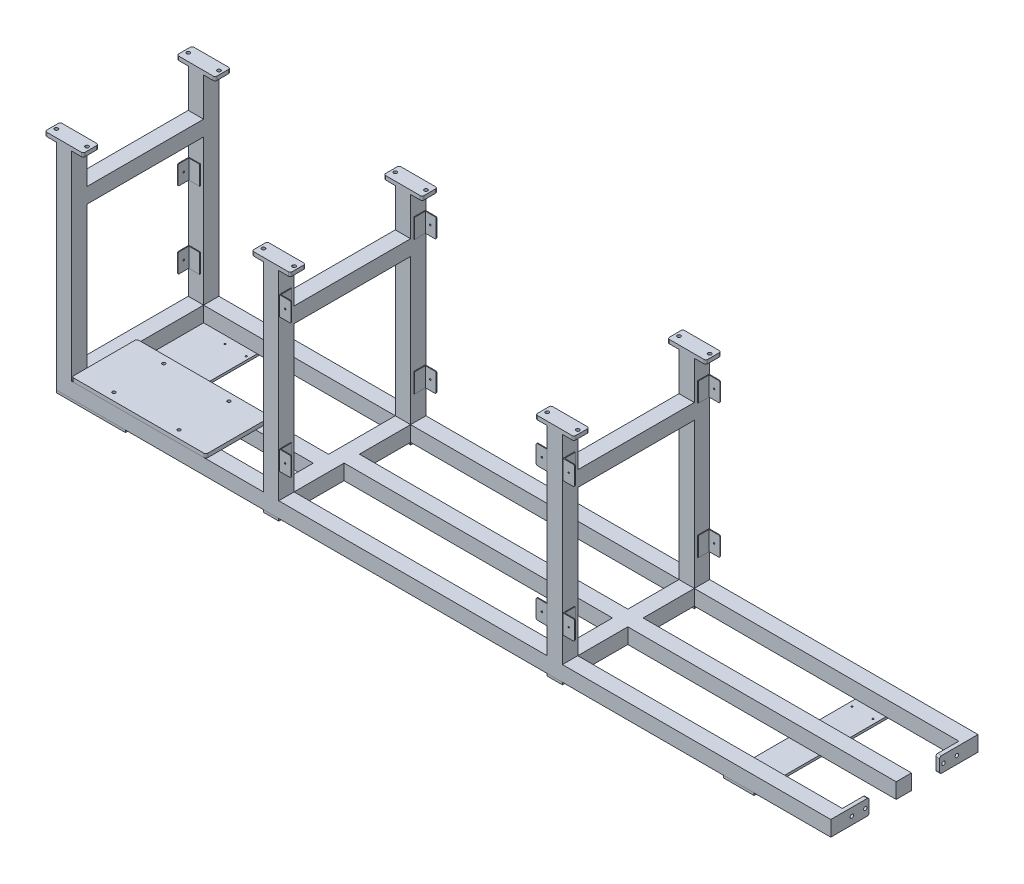
SolidWorks part; units mm, degrees
ref_plane "前视基准面" through (0, 0, 0) normal (0, 0, 1) x (1, 0, 0)
ref_plane "上视基准面" through (0, 0, 0) normal (0, 1, 0) x (1, 0, 0)
ref_plane "右视基准面" through (0, 0, 0) normal (1, 0, 0) x (0, 0, -1)
sketch "草图1" plane through (0, 0, 0) normal (0, 0, 1) x (1, 0, 0)
  line L0 (-10593.7643, -35429.2791) -> (-9893.7643, -35429.2791)
  line L1 (-10593.7643, -35389.2791) -> (-9893.7643, -35389.2791)
  line L2 (-10593.7643, -35394.2791) -> (-9893.7643, -35394.2791) construction
  line L3 (-10593.7643, -35424.2791) -> (-9893.7643, -35424.2791) construction
  line L4 (-9893.7643, -34869.2791) -> (-9893.7643, -35429.2791)
  line L5 (-9888.7643, -34869.2791) -> (-9888.7643, -35429.2791) construction
  line L6 (-9893.7643, -35429.2791) -> (-9853.7643, -35429.2791)
  line L7 (-9888.7643, -35419.2791) -> (-9858.7643, -35419.2791) construction
  line L8 (-9853.7643, -35429.2791) -> (-9853.7643, -34869.2791)
  line L9 (-9858.7643, -35429.2791) -> (-9858.7643, -34869.2791) construction
  line L10 (-9923.7643, -34859.2791) -> (-9823.7643, -34859.2791)
  line L11 (-9923.7643, -34869.2791) -> (-9823.7643, -34869.2791)
  line L12 (-9923.7643, -34859.2791) -> (-9923.7643, -34869.2791)
  line L13 (-9823.7643, -34859.2791) -> (-9823.7643, -34869.2791)
  line L14 (-9873.7643, -35408.8074) -> (-9873.7643, -35438.7532) construction
  line L15 (-9881.7643, -35419.2791) -> (-9881.7643, -35429.2791) construction
  line L16 (-9880.2643, -35419.2791) -> (-9880.2643, -35429.2791) construction
  line L17 (-9865.7643, -35419.2791) -> (-9865.7643, -35429.2791) construction
  line L18 (-9867.2643, -35419.2791) -> (-9867.2643, -35429.2791) construction
  line L19 (-9893.7643, -35389.2791) -> (-9853.7643, -35389.2791) construction
  line L20 (-9853.7643, -35389.2791) -> (-9853.7643, -35429.2791) construction
  line L21 (-9853.7643, -35429.2791) -> (-9893.7643, -35429.2791) construction
  line L22 (-9893.7643, -35429.2791) -> (-9893.7643, -35389.2791) construction
  line L23 (-9888.7643, -35394.2791) -> (-9858.7643, -35394.2791) construction
  line L24 (-9858.7643, -35394.2791) -> (-9858.7643, -35424.2791) construction
  line L25 (-9858.7643, -35424.2791) -> (-9888.7643, -35424.2791) construction
  line L26 (-9888.7643, -35424.2791) -> (-9888.7643, -35394.2791) construction
  line L27 (-9893.7643, -34969.2791) -> (-9853.7643, -34969.2791) construction
  line L28 (-9853.7643, -34969.2791) -> (-9853.7643, -35009.2791) construction
  line L29 (-9853.7643, -35009.2791) -> (-9893.7643, -35009.2791) construction
  line L30 (-9893.7643, -35009.2791) -> (-9893.7643, -34969.2791) construction
  line L31 (-9888.7643, -34974.2791) -> (-9858.7643, -34974.2791) construction
  line L32 (-9858.7643, -34974.2791) -> (-9858.7643, -35004.2791) construction
  line L33 (-9858.7643, -35004.2791) -> (-9888.7643, -35004.2791) construction
  line L34 (-9888.7643, -35004.2791) -> (-9888.7643, -34974.2791) construction
  line L35 (-9163.7643, -35429.2791) -> (-9853.7643, -35429.2791)
  line L36 (-9353.7643, -35435.2791) -> (-9433.7643, -35435.2791)
  line L37 (-9163.7643, -35389.2791) -> (-9853.7643, -35389.2791)
  line L38 (-9163.7643, -35394.2791) -> (-9853.7643, -35394.2791) construction
  line L39 (-9163.7643, -35424.2791) -> (-9853.7643, -35424.2791) construction
  line L40 (-11160.7643, -35451.2791) -> (-11160.7643, -35501.2791)
  line L41 (-11161.7643, -35451.2791) -> (-11161.7643, -35501.2791)
  line L42 (-11146.7643, -35451.2791) -> (-11146.7643, -35501.2791)
  line L43 (-11145.7643, -35451.2791) -> (-11145.7643, -35501.2791)
  line L44 (-11183.7643, -35520.2791) -> (-11183.7643, -35521.2791)
  line L45 (-11123.7643, -35520.2791) -> (-11123.7643, -35521.2791)
  line L46 (-11123.7643, -35521.2791) -> (-11183.7643, -35521.2791)
  line L47 (-11123.7643, -35520.2791) -> (-11183.7643, -35520.2791)
  line L48 (-11136.7643, -35511.2791) -> (-11170.7643, -35511.2791)
  line L49 (-11166.7643, -35502.7793) -> (-11166.7643, -35509.7789)
  line L50 (-11161.2643, -35502.7791) -> (-11161.2643, -35509.7793)
  line L51 (-11143.3603, -35501.2791) -> (-11163.982, -35501.2791)
  line L52 (-11143.5143, -35501.2791) -> (-11164.0142, -35501.2791)
  line L53 (-11146.2643, -35502.7791) -> (-11146.2643, -35509.7791)
  line L54 (-11140.7643, -35502.7791) -> (-11140.7643, -35509.7791)
  line L55 (-11161.7643, -35451.2791) -> (-11145.7643, -35451.2791)
  line L56 (-11073.7643, -35462.2791) -> (-11073.7643, -35456.2791)
  line L57 (-11068.7643, -35451.2791) -> (-11018.7643, -35451.2791)
  line L58 (-11008.8614, -35456.2791) -> (-11008.0003, -35462.2791)
  line L59 (-11083.7643, -35441.2791) -> (-10993.7643, -35441.2791)
  line L60 (-10993.7643, -35441.2791) -> (-10993.7643, -35435.2791)
  line L61 (-10993.7643, -35435.2791) -> (-11083.7643, -35435.2791)
  line L62 (-11083.7643, -35435.2791) -> (-11083.7643, -35441.2791)
  line L63 (-11068.7643, -35441.2791) -> (-11068.7643, -35451.2791)
  line L64 (-11068.7643, -35451.2791) -> (-11018.7643, -35451.2791)
  line L65 (-11018.7643, -35451.2791) -> (-11018.7643, -35441.2791)
  line L66 (-11018.7643, -35441.2791) -> (-11068.7643, -35441.2791)
  line L67 (-11073.7643, -35462.2791) -> (-11073.7643, -35456.2791)
  line L68 (-11068.7643, -35451.2791) -> (-11018.7643, -35451.2791)
  line L69 (-11008.8614, -35456.2791) -> (-11008.0003, -35462.2791)
  line L70 (-11083.7643, -35441.2791) -> (-10993.7643, -35441.2791)
  line L71 (-10993.7643, -35441.2791) -> (-10993.7643, -35435.2791)
  line L72 (-10993.7643, -35435.2791) -> (-11083.7643, -35435.2791)
  line L73 (-11083.7643, -35435.2791) -> (-11083.7643, -35441.2791)
  line L74 (-11068.7643, -35441.2791) -> (-11068.7643, -35451.2791)
  line L75 (-11068.7643, -35451.2791) -> (-11018.7643, -35451.2791)
  line L76 (-11018.7643, -35451.2791) -> (-11018.7643, -35441.2791)
  line L77 (-11018.7643, -35441.2791) -> (-11068.7643, -35441.2791)
  line L78 (-10633.7643, -34869.2791) -> (-10633.7643, -35429.2791)
  line L79 (-10628.7643, -34869.2791) -> (-10628.7643, -35429.2791) construction
  line L80 (-10633.7643, -35429.2791) -> (-10593.7643, -35429.2791)
  line L81 (-10593.7643, -35429.2791) -> (-10593.7643, -34869.2791)
  line L82 (-10598.7643, -35429.2791) -> (-10598.7643, -34869.2791) construction
  line L83 (-10663.7643, -34859.2791) -> (-10563.7643, -34859.2791)
  line L84 (-10663.7643, -34869.2791) -> (-10563.7643, -34869.2791)
  line L85 (-10663.7643, -34859.2791) -> (-10663.7643, -34869.2791)
  line L86 (-10563.7643, -34859.2791) -> (-10563.7643, -34869.2791)
  line L87 (-10633.7643, -35389.2791) -> (-10593.7643, -35389.2791) construction
  line L88 (-10593.7643, -35389.2791) -> (-10593.7643, -35429.2791) construction
  line L89 (-10593.7643, -35429.2791) -> (-10633.7643, -35429.2791) construction
  line L90 (-10633.7643, -35429.2791) -> (-10633.7643, -35389.2791) construction
  line L91 (-10628.7643, -35394.2791) -> (-10598.7643, -35394.2791) construction
  line L92 (-10598.7643, -35394.2791) -> (-10598.7643, -35424.2791) construction
  line L93 (-10598.7643, -35424.2791) -> (-10628.7643, -35424.2791) construction
  line L94 (-10628.7643, -35424.2791) -> (-10628.7643, -35394.2791) construction
  line L95 (-10633.7643, -34969.2791) -> (-10593.7643, -34969.2791) construction
  line L96 (-10593.7643, -34969.2791) -> (-10593.7643, -35009.2791) construction
  line L97 (-10593.7643, -35009.2791) -> (-10633.7643, -35009.2791) construction
  line L98 (-10633.7643, -35009.2791) -> (-10633.7643, -34969.2791) construction
  line L99 (-10628.7643, -34974.2791) -> (-10598.7643, -34974.2791) construction
  line L100 (-10598.7643, -34974.2791) -> (-10598.7643, -35004.2791) construction
  line L101 (-10598.7643, -35004.2791) -> (-10628.7643, -35004.2791) construction
  line L102 (-10628.7643, -35004.2791) -> (-10628.7643, -34974.2791) construction
  line L103 (-11173.7643, -34869.2791) -> (-11173.7643, -35429.2791)
  line L104 (-11168.7643, -34869.2791) -> (-11168.7643, -35429.2791) construction
  line L105 (-11173.7643, -35429.2791) -> (-11133.7643, -35429.2791)
  line L106 (-11133.7643, -35429.2791) -> (-11133.7643, -34869.2791)
  line L107 (-11138.7643, -35429.2791) -> (-11138.7643, -34869.2791) construction
  line L108 (-11203.7643, -34859.2791) -> (-11103.7643, -34859.2791)
  line L109 (-11203.7643, -34869.2791) -> (-11103.7643, -34869.2791)
  line L110 (-11203.7643, -34859.2791) -> (-11203.7643, -34869.2791)
  line L111 (-11103.7643, -34859.2791) -> (-11103.7643, -34869.2791)
  line L112 (-11153.7643, -35408.8074) -> (-11153.7643, -35462.6945) construction
  line L113 (-11173.7643, -35389.2791) -> (-11133.7643, -35389.2791) construction
  line L114 (-11133.7643, -35389.2791) -> (-11133.7643, -35429.2791) construction
  line L115 (-11133.7643, -35429.2791) -> (-11173.7643, -35429.2791) construction
  line L116 (-11173.7643, -35429.2791) -> (-11173.7643, -35389.2791) construction
  line L117 (-11168.7643, -35394.2791) -> (-11138.7643, -35394.2791) construction
  line L118 (-11138.7643, -35394.2791) -> (-11138.7643, -35424.2791) construction
  line L119 (-11138.7643, -35424.2791) -> (-11168.7643, -35424.2791) construction
  line L120 (-11168.7643, -35424.2791) -> (-11168.7643, -35394.2791) construction
  line L121 (-11173.7643, -34969.2791) -> (-11133.7643, -34969.2791) construction
  line L122 (-11133.7643, -34969.2791) -> (-11133.7643, -35009.2791) construction
  line L123 (-11133.7643, -35009.2791) -> (-11173.7643, -35009.2791) construction
  line L124 (-11173.7643, -35009.2791) -> (-11173.7643, -34969.2791) construction
  line L125 (-11168.7643, -34974.2791) -> (-11138.7643, -34974.2791) construction
  line L126 (-11138.7643, -34974.2791) -> (-11138.7643, -35004.2791) construction
  line L127 (-11138.7643, -35004.2791) -> (-11168.7643, -35004.2791) construction
  line L128 (-11168.7643, -35004.2791) -> (-11168.7643, -34974.2791) construction
  line L129 (-11133.7643, -35389.2791) -> (-10633.7643, -35389.2791)
  line L130 (-11133.7643, -35394.2791) -> (-10633.7643, -35394.2791) construction
  line L131 (-11133.7643, -35429.2791) -> (-10633.7643, -35429.2791)
  line L132 (-10628.7643, -35419.2791) -> (-10598.7643, -35419.2791) construction
  line L133 (-11133.7643, -35424.2791) -> (-10633.7643, -35424.2791) construction
  line L134 (-10783.7643, -35389.2791) -> (-10783.7643, -35379.2791)
  line L135 (-10783.7643, -35379.2791) -> (-11133.7643, -35379.2791)
  line L136 (-10873.7643, -35400.5647) -> (-10873.7643, -35369.9687) construction
  line L137 (-11043.7643, -35400.5647) -> (-11043.7643, -35369.9687) construction
  line L138 (-11173.7643, -35429.2791) -> (-10993.7643, -35429.2791)
  line L139 (-10993.7643, -35429.2791) -> (-10993.7643, -35435.2791)
  line L140 (-10993.7643, -35435.2791) -> (-11173.7643, -35435.2791)
  line L141 (-11173.7643, -35429.2791) -> (-11173.7643, -35435.2791)
  line L142 (-10613.7643, -35429.2791) -> (-10613.7643, -35414.98) construction
  line L143 (-10605.7643, -35429.2791) -> (-10605.7643, -35419.2791) construction
  line L144 (-10606.7643, -35429.2791) -> (-10606.7643, -35419.2791) construction
  line L145 (-10621.7643, -35429.2791) -> (-10621.7643, -35419.2791) construction
  line L146 (-10620.7643, -35429.2791) -> (-10620.7643, -35419.2791) construction
  line L147 (-11146.8361, -35437.2791) -> (-11146.8361, -35449.2791)
  line L148 (-11160.6925, -35437.2791) -> (-11160.6925, -35449.2791)
  line L149 (-11143.372, -35451.2791) -> (-11164.1566, -35451.2791)
  line L150 (-11139.9079, -35437.2791) -> (-11139.9079, -35449.2791)
  line L151 (-11167.6207, -35437.2791) -> (-11167.6207, -35449.2791)
  line L152 (-11143.372, -35435.2791) -> (-11164.1566, -35435.2791)
  line L153 (-10620.7643, -35429.2791) -> (-10620.7643, -35501.2791)
  line L154 (-10621.7643, -35429.2791) -> (-10621.7643, -35501.2791)
  line L155 (-10606.7643, -35429.2791) -> (-10606.7643, -35501.2791)
  line L156 (-10605.7643, -35429.2791) -> (-10605.7643, -35501.2791)
  line L157 (-10643.7643, -35520.2791) -> (-10643.7643, -35521.2791)
  line L158 (-10583.7643, -35520.2791) -> (-10583.7643, -35521.2791)
  line L159 (-10583.7643, -35521.2791) -> (-10643.7643, -35521.2791)
  line L160 (-10583.7643, -35520.2791) -> (-10643.7643, -35520.2791)
  line L161 (-10596.7643, -35511.2791) -> (-10630.7643, -35511.2791)
  line L162 (-10626.7643, -35502.7793) -> (-10626.7643, -35509.7789)
  line L163 (-10621.2643, -35502.7791) -> (-10621.2643, -35509.7793)
  line L164 (-10603.3603, -35501.2791) -> (-10623.982, -35501.2791)
  line L165 (-10603.5143, -35501.2791) -> (-10624.0142, -35501.2791)
  line L166 (-10606.2643, -35502.7791) -> (-10606.2643, -35509.7791)
  line L167 (-10600.7643, -35502.7791) -> (-10600.7643, -35509.7791)
  line L168 (-10621.7643, -35429.2791) -> (-10605.7643, -35429.2791)
  line L169 (-9880.7643, -35429.2791) -> (-9880.7643, -35501.2791)
  line L170 (-9881.7643, -35429.2791) -> (-9881.7643, -35501.2791)
  line L171 (-9866.7643, -35429.2791) -> (-9866.7643, -35501.2791)
  line L172 (-9865.7643, -35429.2791) -> (-9865.7643, -35501.2791)
  line L173 (-9903.7643, -35520.2791) -> (-9903.7643, -35521.2791)
  line L174 (-9843.7643, -35520.2791) -> (-9843.7643, -35521.2791)
  line L175 (-9843.7643, -35521.2791) -> (-9903.7643, -35521.2791)
  line L176 (-9843.7643, -35520.2791) -> (-9903.7643, -35520.2791)
  line L177 (-9856.7643, -35511.2791) -> (-9890.7643, -35511.2791)
  line L178 (-9886.7643, -35502.7793) -> (-9886.7643, -35509.7789)
  line L179 (-9881.2643, -35502.7791) -> (-9881.2643, -35509.7793)
  line L180 (-9863.3603, -35501.2791) -> (-9883.982, -35501.2791)
  line L181 (-9863.5143, -35501.2791) -> (-9884.0142, -35501.2791)
  line L182 (-9866.2643, -35502.7791) -> (-9866.2643, -35509.7791)
  line L183 (-9860.7643, -35502.7791) -> (-9860.7643, -35509.7791)
  line L184 (-9881.7643, -35429.2791) -> (-9865.7643, -35429.2791)
  line L185 (-9353.7643, -35435.2791) -> (-9353.7643, -35429.2791)
  line L186 (-9433.7643, -35435.2791) -> (-9433.7643, -35429.2791)
  line L187 (-9358.7643, -35462.2791) -> (-9358.7643, -35456.2791)
  line L188 (-9363.7643, -35451.2791) -> (-9413.7643, -35451.2791)
  line L189 (-9423.6672, -35456.2791) -> (-9424.5283, -35462.2791)
  line L190 (-9358.7643, -35441.2791) -> (-9428.7643, -35441.2791)
  line L191 (-9428.7643, -35441.2791) -> (-9428.7643, -35435.2791)
  line L192 (-9428.7643, -35435.2791) -> (-9358.7643, -35435.2791)
  line L193 (-9358.7643, -35435.2791) -> (-9358.7643, -35441.2791)
  line L194 (-9363.7643, -35441.2791) -> (-9363.7643, -35451.2791)
  line L195 (-9363.7643, -35451.2791) -> (-9413.7643, -35451.2791)
  line L196 (-9413.7643, -35451.2791) -> (-9413.7643, -35441.2791)
  line L197 (-9413.7643, -35441.2791) -> (-9363.7643, -35441.2791)
  line L198 (-9358.7643, -35462.2791) -> (-9358.7643, -35456.2791)
  line L199 (-9363.7643, -35451.2791) -> (-9413.7643, -35451.2791)
  line L200 (-9423.6672, -35456.2791) -> (-9424.5283, -35462.2791)
  line L201 (-9358.7643, -35441.2791) -> (-9428.7643, -35441.2791)
  line L202 (-9428.7643, -35441.2791) -> (-9428.7643, -35435.2791)
  line L203 (-9428.7643, -35435.2791) -> (-9358.7643, -35435.2791)
  line L204 (-9358.7643, -35435.2791) -> (-9358.7643, -35441.2791)
  line L205 (-9363.7643, -35441.2791) -> (-9363.7643, -35451.2791)
  line L206 (-9363.7643, -35451.2791) -> (-9413.7643, -35451.2791)
  line L207 (-9413.7643, -35451.2791) -> (-9413.7643, -35441.2791)
  line L208 (-9413.7643, -35441.2791) -> (-9363.7643, -35441.2791)
  line L209 (-10593.7643, -34924.2791) -> (-10566.7643, -34924.2791)
  line L210 (-10563.7643, -34927.2791) -> (-10563.7643, -34971.2791)
  line L211 (-10566.7643, -34974.2791) -> (-10593.7643, -34974.2791)
  line L212 (-10593.7643, -34974.2791) -> (-10593.7643, -34924.2791)
  line L213 (-10591.7643, -34974.2791) -> (-10591.7643, -34924.2791) construction
  line L214 (-10593.7643, -35273.2791) -> (-10566.7643, -35273.2791)
  line L215 (-10563.7643, -35276.2791) -> (-10563.7643, -35320.2791)
  line L216 (-10566.7643, -35323.2791) -> (-10593.7643, -35323.2791)
  line L217 (-10593.7643, -35323.2791) -> (-10593.7643, -35273.2791)
  line L218 (-10591.7643, -35323.2791) -> (-10591.7643, -35273.2791) construction
  line L219 (-9893.7643, -34924.2791) -> (-9920.7643, -34924.2791)
  line L220 (-9923.7643, -34927.2791) -> (-9923.7643, -34971.2791)
  line L221 (-9920.7643, -34974.2791) -> (-9893.7643, -34974.2791)
  line L222 (-9893.7643, -34974.2791) -> (-9893.7643, -34924.2791)
  line L223 (-9895.7643, -34974.2791) -> (-9895.7643, -34924.2791) construction
  line L224 (-9893.7643, -35273.2791) -> (-9920.7643, -35273.2791)
  line L225 (-9923.7643, -35276.2791) -> (-9923.7643, -35320.2791)
  line L226 (-9920.7643, -35323.2791) -> (-9893.7643, -35323.2791)
  line L227 (-9893.7643, -35323.2791) -> (-9893.7643, -35273.2791)
  line L228 (-9895.7643, -35323.2791) -> (-9895.7643, -35273.2791) construction
  line L229 (-9853.7643, -34924.2791) -> (-9826.7643, -34924.2791)
  line L230 (-9823.7643, -34927.2791) -> (-9823.7643, -34971.2791)
  line L231 (-9826.7643, -34974.2791) -> (-9853.7643, -34974.2791)
  line L232 (-9853.7643, -34974.2791) -> (-9853.7643, -34924.2791)
  line L233 (-9851.7643, -34974.2791) -> (-9851.7643, -34924.2791) construction
  line L234 (-9853.7643, -35273.2791) -> (-9826.7643, -35273.2791)
  line L235 (-9823.7643, -35276.2791) -> (-9823.7643, -35320.2791)
  line L236 (-9826.7643, -35323.2791) -> (-9853.7643, -35323.2791)
  line L237 (-9853.7643, -35323.2791) -> (-9853.7643, -35273.2791)
  line L238 (-9851.7643, -35323.2791) -> (-9851.7643, -35273.2791) construction
  line L239 (-9163.7643, -35389.2791) -> (-9163.7643, -35429.2791)
  line L240 (-9163.7643, -35429.2791) -> (-9153.7643, -35429.2791)
  line L241 (-9153.7643, -35429.2791) -> (-9153.7643, -35389.2791)
  line L242 (-9163.7643, -35389.2791) -> (-9153.7643, -35389.2791)
  line L243 (-9176.3845, -35409.2791) -> (-9142.5729, -35409.2791) construction
  arc A0 (-11146.2643, -35509.7791) -> (-11140.7643, -35509.7791) centre (-11143.5143, -35508.0083) ccw
  arc A1 (-11128.7643, -35520.2791) -> (-11136.7643, -35511.2791) centre (-11147.4334, -35528.8183) ccw
  arc A2 (-11161.2643, -35509.7791) -> (-11146.2643, -35509.7791) centre (-11153.7643, -35491.7791) ccw
  arc A3 (-11166.7642, -35509.7791) -> (-11161.2642, -35509.7791) centre (-11164.0142, -35508.0083) ccw
  arc A4 (-11170.764, -35511.2791) -> (-11178.764, -35520.2791) centre (-11160.0949, -35528.8183) ccw
  arc A5 (-11161.2642, -35502.7791) -> (-11166.7642, -35502.7791) centre (-11164.0142, -35504.55) ccw
  arc A6 (-11146.2643, -35502.7791) -> (-11161.2643, -35502.7791) centre (-11153.7643, -35520.7791) ccw
  arc A7 (-11140.7643, -35502.7791) -> (-11146.2643, -35502.7791) centre (-11143.5143, -35504.55) ccw
  arc A8 (-11068.7643, -35451.2791) -> (-11073.7643, -35456.2791) centre (-11068.7643, -35456.2791) ccw
  arc A9 (-11008.8614, -35456.2791) -> (-11018.7643, -35451.2791) centre (-11018.2173, -35462.5025) ccw
  arc A10 (-11040.374, -35474.8886) -> (-11007.4614, -35473.0474) centre (-11023.2849, -35485.2791) ccw
  arc A11 (-11047.2576, -35467.2428) -> (-11008.4409, -35459.2089) centre (-11023.2849, -35485.2791) ccw
  circle A12 centre (-11023.2849, -35485.2791) radius 6
  arc A13 (-11068.7643, -35451.2791) -> (-11073.7643, -35456.2791) centre (-11068.7643, -35456.2791) ccw
  arc A14 (-11008.8614, -35456.2791) -> (-11018.7643, -35451.2791) centre (-11018.2173, -35462.5025) ccw
  arc A15 (-11040.374, -35474.8886) -> (-11007.4614, -35473.0474) centre (-11023.2849, -35485.2791) ccw
  arc A16 (-11047.2576, -35467.2428) -> (-11008.4409, -35459.2089) centre (-11023.2849, -35485.2791) ccw
  circle A17 centre (-11023.2849, -35485.2791) radius 6
  arc A18 (-10606.2643, -35509.7791) -> (-10600.7643, -35509.7791) centre (-10603.5143, -35508.0083) ccw
  arc A19 (-10588.7643, -35520.2791) -> (-10596.7643, -35511.2791) centre (-10607.4334, -35528.8183) ccw
  arc A20 (-10621.2643, -35509.7791) -> (-10606.2643, -35509.7791) centre (-10613.7643, -35491.7791) ccw
  arc A21 (-10626.7642, -35509.7791) -> (-10621.2642, -35509.7791) centre (-10624.0142, -35508.0083) ccw
  arc A22 (-10630.7641, -35511.2791) -> (-10638.7641, -35520.2791) centre (-10620.095, -35528.8183) ccw
  arc A23 (-10621.2642, -35502.7791) -> (-10626.7642, -35502.7791) centre (-10624.0142, -35504.55) ccw
  arc A24 (-10606.2643, -35502.7791) -> (-10621.2643, -35502.7791) centre (-10613.7643, -35520.7791) ccw
  arc A25 (-10600.7643, -35502.7791) -> (-10606.2643, -35502.7791) centre (-10603.5143, -35504.55) ccw
  arc A26 (-9866.2643, -35509.7791) -> (-9860.7643, -35509.7791) centre (-9863.5143, -35508.0083) ccw
  arc A27 (-9848.7643, -35520.2791) -> (-9856.7643, -35511.2791) centre (-9867.4334, -35528.8183) ccw
  arc A28 (-9881.2643, -35509.7791) -> (-9866.2643, -35509.7791) centre (-9873.7643, -35491.7791) ccw
  arc A29 (-9886.7642, -35509.7791) -> (-9881.2642, -35509.7791) centre (-9884.0142, -35508.0083) ccw
  arc A30 (-9890.7641, -35511.2791) -> (-9898.7641, -35520.2791) centre (-9880.095, -35528.8183) ccw
  arc A31 (-9881.2642, -35502.7791) -> (-9886.7642, -35502.7791) centre (-9884.0142, -35504.55) ccw
  arc A32 (-9866.2643, -35502.7791) -> (-9881.2643, -35502.7791) centre (-9873.7643, -35520.7791) ccw
  arc A33 (-9860.7643, -35502.7791) -> (-9866.2643, -35502.7791) centre (-9863.5143, -35504.55) ccw
  arc A34 (-9358.7643, -35456.2791) -> (-9363.7643, -35451.2791) centre (-9363.7643, -35456.2791) ccw
  arc A35 (-9413.7643, -35451.2791) -> (-9423.6672, -35456.2791) centre (-9414.3113, -35462.5025) ccw
  arc A36 (-9425.0673, -35473.0474) -> (-9392.1547, -35474.8886) centre (-9409.2437, -35485.2791) ccw
  arc A37 (-9424.0877, -35459.2089) -> (-9385.271, -35467.2428) centre (-9409.2437, -35485.2791) ccw
  circle A38 centre (-9409.2437, -35485.2791) radius 6
  arc A39 (-9358.7643, -35456.2791) -> (-9363.7643, -35451.2791) centre (-9363.7643, -35456.2791) ccw
  arc A40 (-9413.7643, -35451.2791) -> (-9423.6672, -35456.2791) centre (-9414.3113, -35462.5025) ccw
  arc A41 (-9425.0673, -35473.0474) -> (-9392.1547, -35474.8886) centre (-9409.2437, -35485.2791) ccw
  arc A42 (-9424.0877, -35459.2089) -> (-9385.271, -35467.2428) centre (-9409.2437, -35485.2791) ccw
  circle A43 centre (-9409.2437, -35485.2791) radius 6
  arc A44 (-10563.7643, -34927.2791) -> (-10566.7643, -34924.2791) centre (-10566.7643, -34927.2791) ccw
  arc A45 (-10566.7643, -34974.2791) -> (-10563.7643, -34971.2791) centre (-10566.7643, -34971.2791) ccw
  arc A46 (-10576.2643, -34949.2791) -> (-10578.7643, -34951.7791) centre (-10578.7643, -34949.2791) ccw
  circle A47 centre (-10578.7643, -34949.2791) radius 2
  arc A48 (-10563.7643, -35276.2791) -> (-10566.7643, -35273.2791) centre (-10566.7643, -35276.2791) ccw
  arc A49 (-10566.7643, -35323.2791) -> (-10563.7643, -35320.2791) centre (-10566.7643, -35320.2791) ccw
  arc A50 (-10576.2643, -35298.2791) -> (-10578.7643, -35300.7791) centre (-10578.7643, -35298.2791) ccw
  circle A51 centre (-10578.7643, -35298.2791) radius 2
  arc A52 (-9920.7643, -34924.2791) -> (-9923.7643, -34927.2791) centre (-9920.7643, -34927.2791) ccw
  arc A53 (-9923.7643, -34971.2791) -> (-9920.7643, -34974.2791) centre (-9920.7643, -34971.2791) ccw
  arc A54 (-9908.7643, -34951.7791) -> (-9911.2643, -34949.2791) centre (-9908.7643, -34949.2791) ccw
  circle A55 centre (-9908.7643, -34949.2791) radius 2
  arc A56 (-9920.7643, -35273.2791) -> (-9923.7643, -35276.2791) centre (-9920.7643, -35276.2791) ccw
  arc A57 (-9923.7643, -35320.2791) -> (-9920.7643, -35323.2791) centre (-9920.7643, -35320.2791) ccw
  arc A58 (-9908.7643, -35300.7791) -> (-9911.2643, -35298.2791) centre (-9908.7643, -35298.2791) ccw
  circle A59 centre (-9908.7643, -35298.2791) radius 2
  arc A60 (-9823.7643, -34927.2791) -> (-9826.7643, -34924.2791) centre (-9826.7643, -34927.2791) ccw
  arc A61 (-9826.7643, -34974.2791) -> (-9823.7643, -34971.2791) centre (-9826.7643, -34971.2791) ccw
  arc A62 (-9836.2643, -34949.2791) -> (-9838.7643, -34951.7791) centre (-9838.7643, -34949.2791) ccw
  circle A63 centre (-9838.7643, -34949.2791) radius 2
  arc A64 (-9823.7643, -35276.2791) -> (-9826.7643, -35273.2791) centre (-9826.7643, -35276.2791) ccw
  arc A65 (-9826.7643, -35323.2791) -> (-9823.7643, -35320.2791) centre (-9826.7643, -35320.2791) ccw
  arc A66 (-9836.2643, -35298.2791) -> (-9838.7643, -35300.7791) centre (-9838.7643, -35298.2791) ccw
  circle A67 centre (-9838.7643, -35298.2791) radius 2
  spline S0 degree 3 poles (-11073.7643, -35462.2791) (-11070.0085, -35462.0751) (-11058.0972, -35461.4281) (-11037.2738, -35469.7417) (-11038.7439, -35496.073) (-11010.5932, -35496.8112) (-11006.86, -35477.1965) (-11007.6341, -35467.0699) (-11008.0003, -35462.2791) knots 0 0 0 0 0.107435 0.340721 0.514208 0.707478 0.861613 1 1 1 1
  spline S1 degree 3 poles (-11073.7643, -35462.2791) (-11070.0085, -35462.0751) (-11058.0972, -35461.4281) (-11037.2738, -35469.7417) (-11038.7439, -35496.073) (-11010.5932, -35496.8112) (-11006.86, -35477.1965) (-11007.6341, -35467.0699) (-11008.0003, -35462.2791) knots 0 0 0 0 0.107435 0.340721 0.514208 0.707478 0.861613 1 1 1 1
  spline S2 degree 3 poles (-11139.9079, -35449.2791) (-11141.0626, -35450.2791) (-11143.372, -35452.2791) (-11145.6814, -35450.2791) (-11146.8361, -35449.2791) knots 0 0 0 0 0.5 1 1 1 1
  spline S3 degree 3 poles (-11146.8361, -35449.2791) (-11149.1455, -35450.2791) (-11153.7643, -35452.2791) (-11158.3831, -35450.2791) (-11160.6925, -35449.2791) knots 0 0 0 0 0.5 1 1 1 1
  spline S4 degree 3 poles (-11167.6207, -35449.2791) (-11166.466, -35450.2791) (-11164.1566, -35452.2791) (-11161.8472, -35450.2791) (-11160.6925, -35449.2791) knots 0 0 0 0 0.5 1 1 1 1
  spline S5 degree 3 poles (-11146.8361, -35437.2791) (-11149.1455, -35436.2791) (-11153.7643, -35434.2791) (-11158.3831, -35436.2791) (-11160.6925, -35437.2791) knots 0 0 0 0 0.5 1 1 1 1
  spline S6 degree 3 poles (-11139.9079, -35437.2791) (-11141.0626, -35436.2791) (-11143.372, -35434.2791) (-11145.6814, -35436.2791) (-11146.8361, -35437.2791) knots 0 0 0 0 0.5 1 1 1 1
  spline S7 degree 3 poles (-11167.6207, -35437.2791) (-11166.466, -35436.2791) (-11164.1566, -35434.2791) (-11161.8472, -35436.2791) (-11160.6925, -35437.2791) knots 0 0 0 0 0.5 1 1 1 1
  spline S8 degree 3 poles (-9358.7643, -35462.2791) (-9362.5201, -35462.0751) (-9374.4314, -35461.4281) (-9395.2549, -35469.7417) (-9393.7847, -35496.073) (-9421.9354, -35496.8112) (-9425.6686, -35477.1965) (-9424.8945, -35467.0699) (-9424.5283, -35462.2791) knots 0 0 0 0 11.455017 36.32866 54.826358 75.433281 91.867632 106.622864 106.622864 106.622864 106.622864
  spline S9 degree 3 poles (-9358.7643, -35462.2791) (-9362.5201, -35462.0751) (-9374.4314, -35461.4281) (-9395.2549, -35469.7417) (-9393.7847, -35496.073) (-9421.9354, -35496.8112) (-9425.6686, -35477.1965) (-9424.8945, -35467.0699) (-9424.5283, -35462.2791) knots 0 0 0 0 11.455017 36.32866 54.826358 75.433281 91.867632 106.622864 106.622864 106.622864 106.622864
extrude "凸台-拉伸1" add sketch "草图1" against normal blind 40 contours L111 L108 L110 L109 | L109 L103 L105 L106 | L86 L83 L85 L84 | L84 L78 L80 L81 | L11 L4 L6 L8 | L239 L37 L8 L35 | L81 L0 L4 L1 | L106 L131 L78 L129 | L242 L239 L240 L241 | L10 L13 L11 L12 region at (-10243.7643, -35409.2791, 0) region at (-10613.7643, -35149.2791, 0) region at (-9873.7643, -35149.2791, 0) region at (-10883.7643, -35409.2791, 0) region at (-9508.7643, -35409.2791, 0) region at (-10613.7643, -34864.2791, 0) region at (-11153.7643, -35149.2791, 0) region at (-9158.7643, -35409.2791, 0) region at (-11153.7643, -34864.2791, 0)
sketch "草图2" plane through (0, 0, 0) normal (0, 0, 1) x (1, 0, 0)
  line L1 (-11173.7643, -34969.2791) -> (-11133.7643, -34969.2791)
  line L2 (-11173.7643, -34969.2791) -> (-11173.7643, -35009.2791)
  line L3 (-11173.7643, -35009.2791) -> (-11133.7643, -35009.2791)
  line L4 (-11133.7643, -34969.2791) -> (-11133.7643, -35009.2791)
  line L5 (-10633.7643, -34969.2791) -> (-10593.7643, -34969.2791)
  line L6 (-10633.7643, -34969.2791) -> (-10633.7643, -35009.2791)
  line L7 (-10633.7643, -35009.2791) -> (-10593.7643, -35009.2791)
  line L8 (-10593.7643, -34969.2791) -> (-10593.7643, -35009.2791)
  line L9 (-10633.7643, -35389.2791) -> (-10593.7643, -35389.2791)
  line L10 (-10633.7643, -35389.2791) -> (-10633.7643, -35429.2791)
  line L11 (-10633.7643, -35429.2791) -> (-10593.7643, -35429.2791)
  line L12 (-10593.7643, -35389.2791) -> (-10593.7643, -35429.2791)
  line L13 (-11173.7643, -35389.2791) -> (-11133.7643, -35389.2791)
  line L14 (-11173.7643, -35389.2791) -> (-11173.7643, -35429.2791)
  line L15 (-11173.7643, -35429.2791) -> (-11133.7643, -35429.2791)
  line L16 (-11133.7643, -35389.2791) -> (-11133.7643, -35429.2791)
  line L17 (-9893.7643, -34969.2791) -> (-9853.7643, -34969.2791)
  line L18 (-9893.7643, -34969.2791) -> (-9893.7643, -35009.2791)
  line L19 (-9893.7643, -35009.2791) -> (-9853.7643, -35009.2791)
  line L20 (-9853.7643, -34969.2791) -> (-9853.7643, -35009.2791)
  line L21 (-9893.7643, -35389.2791) -> (-9853.7643, -35389.2791)
  line L22 (-9893.7643, -35389.2791) -> (-9893.7643, -35429.2791)
  line L23 (-9893.7643, -35429.2791) -> (-9853.7643, -35429.2791)
  line L24 (-9853.7643, -35389.2791) -> (-9853.7643, -35429.2791)
extrude "凸台-拉伸2" add sketch "草图2" against normal blind 192
sketch "草图3" plane through (0, 0, 0) normal (0, 0, 1) x (1, 0, 0)
  line L1 (-9163.7643, -35389.2791) -> (-9153.7643, -35389.2791)
  line L2 (-9163.7643, -35389.2791) -> (-9163.7643, -35429.2791)
  line L3 (-9163.7643, -35429.2791) -> (-9153.7643, -35429.2791)
  line L4 (-9153.7643, -35389.2791) -> (-9153.7643, -35429.2791)
extrude "凸台-拉伸3" add sketch "草图3" against normal blind 100
sketch "草图4" plane through (0, -34859.2791, 0) normal (0, 1, 0) x (1, 0, 0)
  line L0 (-11173.7643, 40) -> (-11133.7643, 40) construction
  line L1 (-11133.7643, 40) -> (-11133.7643, 0) construction
  line L2 (-11133.7643, 0) -> (-11173.7643, 0) construction
  line L3 (-11173.7643, 0) -> (-11173.7643, 40) construction
  circle A0 centre (-10573.7643, 20) radius 4.5
  circle A1 centre (-10653.7643, 20) radius 4.5
  circle A2 centre (-11113.7643, 20) radius 4.5
  circle A3 centre (-11193.7643, 20) radius 4.5
  circle A4 centre (-9833.7643, 20) radius 4.5
  circle A5 centre (-9913.7643, 20) radius 4.5
  circle A6 centre (-9833.7643, 20) radius 4.5
extrude "切除-拉伸1" cut sketch "草图4" against normal blind 100 contours A3 | A2 | A1 | A0 | A4 | A5 region at (-10573.7643, -34859.2791, -20) region at (-10653.7643, -34859.2791, -20) region at (-11113.7643, -34859.2791, -20) region at (-11193.7643, -34859.2791, -20) region at (-9833.7643, -34859.2791, -20) region at (-9913.7643, -34859.2791, -20)
fillet "圆角1" radius 5 12 edges at (-9823.7643, -34864.2791, -40) (-9923.7643, -34864.2791, -40) (-9923.7643, -34864.2791, 0) (-9823.7643, -34864.2791, 0) (-11203.7643, -34864.2791, -40) (-11203.7643, -34864.2791, 0) (-11103.7643, -34864.2791, -40) (-11103.7643, -34864.2791, 0) (-10663.7643, -34864.2791, -40) (-10663.7643, -34864.2791, 0) (-10563.7643, -34864.2791, 0) (-10563.7643, -34864.2791, -40)
ref_plane "基准面3" through (0, 0, -1.5) normal (0, 0, 1) x (1, 0, 0)
sketch "草图5" plane through (0, 0, -1.5) normal (0, 0, 1) x (1, 0, 0)
  line L0 (-9920.7643, -35323.2791) -> (-9893.7643, -35323.2791) construction
  line L1 (-9923.7643, -35276.2791) -> (-9923.7643, -35320.2791) construction
  line L2 (-9893.7643, -35273.2791) -> (-9920.7643, -35273.2791) construction
  line L3 (-9826.7643, -35323.2791) -> (-9853.7643, -35323.2791) construction
  line L4 (-9823.7643, -35276.2791) -> (-9823.7643, -35320.2791) construction
  line L5 (-9853.7643, -35273.2791) -> (-9826.7643, -35273.2791) construction
  line L6 (-9826.7643, -34974.2791) -> (-9853.7643, -34974.2791) construction
  line L7 (-9823.7643, -34927.2791) -> (-9823.7643, -34971.2791) construction
  line L8 (-9853.7643, -34924.2791) -> (-9826.7643, -34924.2791) construction
  line L9 (-9920.7643, -34974.2791) -> (-9893.7643, -34974.2791) construction
  line L10 (-9923.7643, -34927.2791) -> (-9923.7643, -34971.2791) construction
  line L11 (-9893.7643, -34924.2791) -> (-9920.7643, -34924.2791) construction
  line L12 (-10566.7643, -35323.2791) -> (-10593.7643, -35323.2791) construction
  line L13 (-10563.7643, -35276.2791) -> (-10563.7643, -35320.2791) construction
  line L14 (-10593.7643, -35273.2791) -> (-10566.7643, -35273.2791) construction
  line L15 (-10566.7643, -34974.2791) -> (-10593.7643, -34974.2791) construction
  line L16 (-10563.7643, -34927.2791) -> (-10563.7643, -34971.2791) construction
  line L17 (-10593.7643, -34924.2791) -> (-10566.7643, -34924.2791) construction
  line L18 (-9920.7643, -35323.2791) -> (-9893.7643, -35323.2791)
  line L19 (-9923.7643, -35276.2791) -> (-9923.7643, -35320.2791)
  line L20 (-9893.7643, -35273.2791) -> (-9920.7643, -35273.2791)
  line L21 (-9826.7643, -35323.2791) -> (-9853.7643, -35323.2791)
  line L22 (-9823.7643, -35276.2791) -> (-9823.7643, -35320.2791)
  line L23 (-9853.7643, -35273.2791) -> (-9826.7643, -35273.2791)
  line L24 (-9826.7643, -34974.2791) -> (-9853.7643, -34974.2791)
  line L25 (-9823.7643, -34927.2791) -> (-9823.7643, -34971.2791)
  line L26 (-9853.7643, -34924.2791) -> (-9826.7643, -34924.2791)
  line L27 (-9920.7643, -34974.2791) -> (-9893.7643, -34974.2791)
  line L28 (-9923.7643, -34927.2791) -> (-9923.7643, -34971.2791)
  line L29 (-9893.7643, -34924.2791) -> (-9920.7643, -34924.2791)
  line L30 (-10566.7643, -35323.2791) -> (-10593.7643, -35323.2791)
  line L31 (-10563.7643, -35276.2791) -> (-10563.7643, -35320.2791)
  line L32 (-10593.7643, -35273.2791) -> (-10566.7643, -35273.2791)
  line L33 (-10566.7643, -34974.2791) -> (-10593.7643, -34974.2791)
  line L34 (-10563.7643, -34927.2791) -> (-10563.7643, -34971.2791)
  line L35 (-10593.7643, -34924.2791) -> (-10566.7643, -34924.2791)
  line L36 (-10593.7643, -34924.2791) -> (-10593.7643, -34974.2791)
  line L37 (-10593.7643, -35273.2791) -> (-10593.7643, -35323.2791)
  line L38 (-9853.7643, -35273.2791) -> (-9853.7643, -35323.2791)
  line L39 (-9893.7643, -35273.2791) -> (-9893.7643, -35323.2791)
  line L40 (-9853.7643, -34924.2791) -> (-9853.7643, -34974.2791)
  line L41 (-9893.7643, -34924.2791) -> (-9893.7643, -34974.2791)
  circle A0 centre (-9908.7643, -35298.2791) radius 2 construction
  arc A1 (-9923.7643, -35320.2791) -> (-9920.7643, -35323.2791) centre (-9920.7643, -35320.2791) ccw construction
  arc A2 (-9920.7643, -35273.2791) -> (-9923.7643, -35276.2791) centre (-9920.7643, -35276.2791) ccw construction
  circle A3 centre (-9838.7643, -35298.2791) radius 2 construction
  arc A4 (-9826.7643, -35323.2791) -> (-9823.7643, -35320.2791) centre (-9826.7643, -35320.2791) ccw construction
  arc A5 (-9823.7643, -35276.2791) -> (-9826.7643, -35273.2791) centre (-9826.7643, -35276.2791) ccw construction
  circle A6 centre (-9838.7643, -34949.2791) radius 2 construction
  circle A7 centre (-9908.7643, -34949.2791) radius 2 construction
  arc A8 (-9826.7643, -34974.2791) -> (-9823.7643, -34971.2791) centre (-9826.7643, -34971.2791) ccw construction
  arc A9 (-9823.7643, -34927.2791) -> (-9826.7643, -34924.2791) centre (-9826.7643, -34927.2791) ccw construction
  arc A10 (-9923.7643, -34971.2791) -> (-9920.7643, -34974.2791) centre (-9920.7643, -34971.2791) ccw construction
  arc A11 (-9920.7643, -34924.2791) -> (-9923.7643, -34927.2791) centre (-9920.7643, -34927.2791) ccw construction
  circle A12 centre (-10578.7643, -35298.2791) radius 2 construction
  arc A13 (-10566.7643, -35323.2791) -> (-10563.7643, -35320.2791) centre (-10566.7643, -35320.2791) ccw construction
  arc A14 (-10563.7643, -35276.2791) -> (-10566.7643, -35273.2791) centre (-10566.7643, -35276.2791) ccw construction
  circle A15 centre (-10578.7643, -34949.2791) radius 2 construction
  arc A16 (-10566.7643, -34974.2791) -> (-10563.7643, -34971.2791) centre (-10566.7643, -34971.2791) ccw construction
  arc A17 (-10563.7643, -34927.2791) -> (-10566.7643, -34924.2791) centre (-10566.7643, -34927.2791) ccw construction
  circle A18 centre (-9908.7643, -35298.2791) radius 2
  arc A19 (-9923.7643, -35320.2791) -> (-9920.7643, -35323.2791) centre (-9920.7643, -35320.2791) ccw
  arc A20 (-9920.7643, -35273.2791) -> (-9923.7643, -35276.2791) centre (-9920.7643, -35276.2791) ccw
  circle A21 centre (-9838.7643, -35298.2791) radius 2
  arc A22 (-9826.7643, -35323.2791) -> (-9823.7643, -35320.2791) centre (-9826.7643, -35320.2791) ccw
  arc A23 (-9823.7643, -35276.2791) -> (-9826.7643, -35273.2791) centre (-9826.7643, -35276.2791) ccw
  circle A24 centre (-9838.7643, -34949.2791) radius 2
  circle A25 centre (-9908.7643, -34949.2791) radius 2
  arc A26 (-9826.7643, -34974.2791) -> (-9823.7643, -34971.2791) centre (-9826.7643, -34971.2791) ccw
  arc A27 (-9823.7643, -34927.2791) -> (-9826.7643, -34924.2791) centre (-9826.7643, -34927.2791) ccw
  arc A28 (-9923.7643, -34971.2791) -> (-9920.7643, -34974.2791) centre (-9920.7643, -34971.2791) ccw
  arc A29 (-9920.7643, -34924.2791) -> (-9923.7643, -34927.2791) centre (-9920.7643, -34927.2791) ccw
  circle A30 centre (-10578.7643, -35298.2791) radius 2
  arc A31 (-10566.7643, -35323.2791) -> (-10563.7643, -35320.2791) centre (-10566.7643, -35320.2791) ccw
  arc A32 (-10563.7643, -35276.2791) -> (-10566.7643, -35273.2791) centre (-10566.7643, -35276.2791) ccw
  circle A33 centre (-10578.7643, -34949.2791) radius 2
  arc A34 (-10566.7643, -34974.2791) -> (-10563.7643, -34971.2791) centre (-10566.7643, -34971.2791) ccw
  arc A35 (-10563.7643, -34927.2791) -> (-10566.7643, -34924.2791) centre (-10566.7643, -34927.2791) ccw
extrude "凸台-拉伸4" add sketch "草图5" against normal blind 2
sketch "草图6" plane through (0, 0, -1.5) normal (0, 0, 1) x (1, 0, 0)
  line L1 (-10593.7643, -34924.2791) -> (-10591.7643, -34924.2791)
  line L2 (-10593.7643, -34924.2791) -> (-10593.7643, -34974.2791)
  line L3 (-10593.7643, -34974.2791) -> (-10591.7643, -34974.2791)
  line L4 (-10591.7643, -34924.2791) -> (-10591.7643, -34974.2791)
  line L5 (-10593.7643, -35273.2791) -> (-10591.7643, -35273.2791)
  line L6 (-10593.7643, -35273.2791) -> (-10593.7643, -35323.2791)
  line L7 (-10593.7643, -35323.2791) -> (-10591.7643, -35323.2791)
  line L8 (-10591.7643, -35273.2791) -> (-10591.7643, -35323.2791)
  line L9 (-9893.7643, -35273.2791) -> (-9895.7643, -35273.2791)
  line L10 (-9893.7643, -35273.2791) -> (-9893.7643, -35323.2791)
  line L11 (-9893.7643, -35323.2791) -> (-9895.7643, -35323.2791)
  line L12 (-9895.7643, -35273.2791) -> (-9895.7643, -35323.2791)
  line L13 (-9853.7643, -35273.2791) -> (-9851.7643, -35273.2791)
  line L14 (-9853.7643, -35273.2791) -> (-9853.7643, -35323.2791)
  line L15 (-9853.7643, -35323.2791) -> (-9851.7643, -35323.2791)
  line L16 (-9851.7643, -35273.2791) -> (-9851.7643, -35323.2791)
  line L17 (-9851.7643, -34924.2791) -> (-9853.7643, -34924.2791)
  line L18 (-9851.7643, -34924.2791) -> (-9851.7643, -34974.2791)
  line L19 (-9851.7643, -34974.2791) -> (-9853.7643, -34974.2791)
  line L20 (-9853.7643, -34924.2791) -> (-9853.7643, -34974.2791)
  line L21 (-9895.7643, -34924.2791) -> (-9893.7643, -34924.2791)
  line L22 (-9895.7643, -34924.2791) -> (-9895.7643, -34974.2791)
  line L23 (-9895.7643, -34974.2791) -> (-9893.7643, -34974.2791)
  line L24 (-9893.7643, -34924.2791) -> (-9893.7643, -34974.2791)
extrude "凸台-拉伸5" add sketch "草图6" against normal blind 30
mirror "镜向1" about plane through (0, 0, -192) normal (0, 0, 1) of bodies 111
ref_plane "基准面4" through (-11172.2643, 0, 0) normal (-1, 0, 0) x (0, 0, 1)
sketch "草图7" plane through (-11172.2643, 0, 0) normal (-1, 0, 0) x (0, 0, 1)
  line L0 (-344.0093, -35429.2791) -> (-40.0093, -35429.2791) construction
  line L1 (-344.0093, -35389.2791) -> (-40.0093, -35389.2791) construction
  line L2 (-344.0093, -35394.2791) -> (-40.0093, -35394.2791) construction
  line L3 (-344.0093, -35424.2791) -> (-40.0093, -35424.2791) construction
  line L4 (-344.0093, -35009.2791) -> (-40.0093, -35009.2791) construction
  line L5 (-344.0093, -34969.2791) -> (-40.0093, -34969.2791) construction
  line L6 (-344.0093, -34974.2791) -> (-40.0093, -34974.2791) construction
  line L7 (-344.0093, -35004.2791) -> (-40.0093, -35004.2791) construction
  line L8 (-40.0093, -35389.2791) -> (-0.0093, -35389.2791) construction
  line L9 (-0.0093, -35389.2791) -> (-0.0093, -35429.2791) construction
  line L10 (-0.0093, -35429.2791) -> (-40.0093, -35429.2791) construction
  line L11 (-40.0093, -35429.2791) -> (-40.0093, -35389.2791) construction
  line L12 (-35.0093, -35394.2791) -> (-5.0093, -35394.2791) construction
  line L13 (-5.0093, -35394.2791) -> (-5.0093, -35424.2791) construction
  line L14 (-5.0093, -35424.2791) -> (-35.0093, -35424.2791) construction
  line L15 (-35.0093, -35424.2791) -> (-35.0093, -35394.2791) construction
  line L16 (-344.0093, -35389.2791) -> (-384.0093, -35389.2791) construction
  line L17 (-384.0093, -35389.2791) -> (-384.0093, -35429.2791) construction
  line L18 (-384.0093, -35429.2791) -> (-344.0093, -35429.2791) construction
  line L19 (-344.0093, -35429.2791) -> (-344.0093, -35389.2791) construction
  line L20 (-349.0093, -35394.2791) -> (-379.0093, -35394.2791) construction
  line L21 (-379.0093, -35394.2791) -> (-379.0093, -35424.2791) construction
  line L22 (-379.0093, -35424.2791) -> (-349.0093, -35424.2791) construction
  line L23 (-349.0093, -35424.2791) -> (-349.0093, -35394.2791) construction
  line L24 (-165.0093, -35394.2791) -> (-135.0093, -35394.2791) construction
  line L25 (-135.0093, -35394.2791) -> (-135.0093, -35424.2791) construction
  line L26 (-135.0093, -35424.2791) -> (-165.0093, -35424.2791) construction
  line L27 (-165.0093, -35424.2791) -> (-165.0093, -35394.2791) construction
  line L28 (-170.0093, -35389.2791) -> (-130.0093, -35389.2791) construction
  line L29 (-130.0093, -35389.2791) -> (-130.0093, -35429.2791) construction
  line L30 (-130.0093, -35429.2791) -> (-170.0093, -35429.2791) construction
  line L31 (-170.0093, -35429.2791) -> (-170.0093, -35389.2791) construction
  line L32 (-170.0093, -35379.2791) -> (-0.0093, -35379.2791) construction
  line L33 (-170.0093, -35389.2791) -> (-170.0093, -35379.2791) construction
  line L34 (-20.0093, -35372.9631) -> (-20.0093, -35402.9089) construction
  line L35 (-150.0093, -35372.9631) -> (-150.0093, -35402.9089) construction
  line L36 (-0.0093, -35429.2791) -> (-0.0093, -35435.2791) construction
  line L37 (-0.0093, -35435.2791) -> (-384.0093, -35435.2791) construction
  line L38 (-384.0093, -35429.2791) -> (-384.0093, -35435.2791) construction
  line L39 (-364.0093, -35408.8074) -> (-364.0093, -35462.6945) construction
  line L40 (-357.0811, -35437.2791) -> (-357.0811, -35449.2791) construction
  line L41 (-370.9375, -35437.2791) -> (-370.9375, -35449.2791) construction
  line L42 (-353.617, -35451.2791) -> (-374.4016, -35451.2791) construction
  line L43 (-350.1529, -35437.2791) -> (-350.1529, -35449.2791) construction
  line L44 (-377.8657, -35437.2791) -> (-377.8657, -35449.2791) construction
  line L45 (-353.617, -35435.2791) -> (-374.4016, -35435.2791) construction
  line L46 (-20.0093, -35408.8074) -> (-20.0093, -35462.6945) construction
  line L47 (-13.0811, -35437.2791) -> (-13.0811, -35449.2791) construction
  line L48 (-26.9375, -35437.2791) -> (-26.9375, -35449.2791) construction
  line L49 (-9.617, -35451.2791) -> (-30.4016, -35451.2791) construction
  line L50 (-6.1529, -35437.2791) -> (-6.1529, -35449.2791) construction
  line L51 (-33.8657, -35437.2791) -> (-33.8657, -35449.2791) construction
  line L52 (-9.617, -35435.2791) -> (-30.4016, -35435.2791) construction
  line L53 (-40.0093, -35074.2792) -> (-67.0093, -35074.2792)
  line L54 (-70.0093, -35077.2792) -> (-70.0093, -35121.2792)
  line L55 (-67.0093, -35124.2792) -> (-40.0093, -35124.2792)
  line L56 (-40.0093, -35124.2792) -> (-40.0093, -35074.2792)
  line L57 (-42.0093, -35124.2792) -> (-42.0093, -35074.2792) construction
  line L58 (-344.0093, -35074.2792) -> (-317.0093, -35074.2792)
  line L59 (-314.0093, -35077.2792) -> (-314.0093, -35121.2792)
  line L60 (-317.0093, -35124.2792) -> (-344.0093, -35124.2792)
  line L61 (-344.0093, -35124.2792) -> (-344.0093, -35074.2792)
  line L62 (-342.0093, -35124.2792) -> (-342.0093, -35074.2792) construction
  line L63 (-40.0093, -35323.2791) -> (-67.0093, -35323.2791)
  line L64 (-70.0093, -35320.2791) -> (-70.0093, -35276.2791)
  line L65 (-67.0093, -35273.2791) -> (-40.0093, -35273.2791)
  line L66 (-40.0093, -35273.2791) -> (-40.0093, -35323.2791)
  line L67 (-42.0093, -35273.2791) -> (-42.0093, -35323.2791) construction
  line L68 (-344.0093, -35323.2791) -> (-317.0093, -35323.2791)
  line L69 (-314.0093, -35320.2791) -> (-314.0093, -35276.2791)
  line L70 (-317.0093, -35273.2791) -> (-344.0093, -35273.2791)
  line L71 (-344.0093, -35273.2791) -> (-344.0093, -35323.2791)
  line L72 (-342.0093, -35273.2791) -> (-342.0093, -35323.2791) construction
  arc A0 (-67.0093, -35074.2792) -> (-70.0093, -35077.2792) centre (-67.0093, -35077.2792) ccw
  arc A1 (-70.0093, -35121.2792) -> (-67.0093, -35124.2792) centre (-67.0093, -35121.2792) ccw
  circle A2 centre (-55.0093, -35099.2792) radius 2
  arc A3 (-314.0093, -35077.2792) -> (-317.0093, -35074.2792) centre (-317.0093, -35077.2792) ccw
  arc A4 (-317.0093, -35124.2792) -> (-314.0093, -35121.2792) centre (-317.0093, -35121.2792) ccw
  circle A5 centre (-329.0093, -35099.2792) radius 2
  arc A6 (-70.0093, -35320.2791) -> (-67.0093, -35323.2791) centre (-67.0093, -35320.2791) ccw
  arc A7 (-67.0093, -35273.2791) -> (-70.0093, -35276.2791) centre (-67.0093, -35276.2791) ccw
  circle A8 centre (-55.0093, -35298.2791) radius 2
  arc A9 (-317.0093, -35323.2791) -> (-314.0093, -35320.2791) centre (-317.0093, -35320.2791) ccw
  arc A10 (-314.0093, -35276.2791) -> (-317.0093, -35273.2791) centre (-317.0093, -35276.2791) ccw
  circle A11 centre (-329.0093, -35298.2791) radius 2
  spline S0 degree 3 poles (-350.1529, -35449.2791) (-351.3076, -35450.2791) (-353.617, -35452.2791) (-355.9264, -35450.2791) (-357.0811, -35449.2791) knots 0 0 0 0 0.5 1 1 1 1 construction
  spline S1 degree 3 poles (-357.0811, -35449.2791) (-359.3905, -35450.2791) (-364.0093, -35452.2791) (-368.6281, -35450.2791) (-370.9375, -35449.2791) knots 0 0 0 0 0.5 1 1 1 1 construction
  spline S2 degree 3 poles (-377.8657, -35449.2791) (-376.711, -35450.2791) (-374.4016, -35452.2791) (-372.0922, -35450.2791) (-370.9375, -35449.2791) knots 0 0 0 0 0.5 1 1 1 1 construction
  spline S3 degree 3 poles (-357.0811, -35437.2791) (-359.3905, -35436.2791) (-364.0093, -35434.2791) (-368.6281, -35436.2791) (-370.9375, -35437.2791) knots 0 0 0 0 0.5 1 1 1 1 construction
  spline S4 degree 3 poles (-350.1529, -35437.2791) (-351.3076, -35436.2791) (-353.617, -35434.2791) (-355.9264, -35436.2791) (-357.0811, -35437.2791) knots 0 0 0 0 0.5 1 1 1 1 construction
  spline S5 degree 3 poles (-377.8657, -35437.2791) (-376.711, -35436.2791) (-374.4016, -35434.2791) (-372.0922, -35436.2791) (-370.9375, -35437.2791) knots 0 0 0 0 0.5 1 1 1 1 construction
  spline S6 degree 3 poles (-6.1529, -35449.2791) (-7.3076, -35450.2791) (-9.617, -35452.2791) (-11.9264, -35450.2791) (-13.0811, -35449.2791) knots 0 0 0 0 0.5 1 1 1 1 construction
  spline S7 degree 3 poles (-13.0811, -35449.2791) (-15.3905, -35450.2791) (-20.0093, -35452.2791) (-24.6281, -35450.2791) (-26.9375, -35449.2791) knots 0 0 0 0 0.5 1 1 1 1 construction
  spline S8 degree 3 poles (-33.8657, -35449.2791) (-32.711, -35450.2791) (-30.4016, -35452.2791) (-28.0922, -35450.2791) (-26.9375, -35449.2791) knots 0 0 0 0 0.5 1 1 1 1 construction
  spline S9 degree 3 poles (-13.0811, -35437.2791) (-15.3905, -35436.2791) (-20.0093, -35434.2791) (-24.6281, -35436.2791) (-26.9375, -35437.2791) knots 0 0 0 0 0.5 1 1 1 1 construction
  spline S10 degree 3 poles (-6.1529, -35437.2791) (-7.3076, -35436.2791) (-9.617, -35434.2791) (-11.9264, -35436.2791) (-13.0811, -35437.2791) knots 0 0 0 0 0.5 1 1 1 1 construction
  spline S11 degree 3 poles (-33.8657, -35437.2791) (-32.711, -35436.2791) (-30.4016, -35434.2791) (-28.0922, -35436.2791) (-26.9375, -35437.2791) knots 0 0 0 0 0.5 1 1 1 1 construction
  line B0 (-384.0093, -34869.2791) -> (-384.0093, -35429.2791)
  line B1 (-379.0093, -34869.2791) -> (-379.0093, -35429.2791) construction
  line B2 (-384.0093, -35429.2791) -> (-344.0093, -35429.2791)
  line B3 (-379.0093, -35419.2791) -> (-349.0093, -35419.2791) construction
  line B4 (-344.0093, -35429.2791) -> (-344.0093, -34869.2791)
  line B5 (-349.0093, -35429.2791) -> (-349.0093, -34869.2791) construction
  line B6 (-384.0093, -34859.2791) -> (-344.0093, -34859.2791)
  line B7 (-384.0093, -34869.2791) -> (-344.0093, -34869.2791)
  line B8 (-384.0093, -34859.2791) -> (-384.0093, -34869.2791)
  line B9 (-344.0093, -34859.2791) -> (-344.0093, -34869.2791)
  line B10 (-364.0093, -35408.8074) -> (-364.0093, -35438.7532) construction
  line B11 (-372.0093, -35419.2791) -> (-372.0093, -35429.2791) construction
  line B12 (-370.5093, -35419.2791) -> (-370.5093, -35429.2791) construction
  line B13 (-356.0093, -35419.2791) -> (-356.0093, -35429.2791) construction
  line B14 (-357.5093, -35419.2791) -> (-357.5093, -35429.2791) construction
  line B15 (-364.0093, -34889.0845) -> (-364.0093, -34847.3551) construction
  line B16 (-0.0093, -34869.2791) -> (-0.0093, -35429.2791)
  line B17 (-5.0093, -34869.2791) -> (-5.0093, -35429.2791) construction
  line B18 (-0.0093, -35429.2791) -> (-40.0093, -35429.2791)
  line B19 (-5.0093, -35419.2791) -> (-35.0093, -35419.2791) construction
  line B20 (-40.0093, -35429.2791) -> (-40.0093, -34869.2791)
  line B21 (-35.0093, -35429.2791) -> (-35.0093, -34869.2791) construction
  line B22 (-0.0093, -34859.2791) -> (-40.0093, -34859.2791)
  line B23 (-0.0093, -34869.2791) -> (-40.0093, -34869.2791)
  line B24 (-0.0093, -34859.2791) -> (-0.0093, -34869.2791)
  line B25 (-40.0093, -34859.2791) -> (-40.0093, -34869.2791)
  line B26 (-20.0093, -35408.8074) -> (-20.0093, -35438.7532) construction
  line B27 (-12.0093, -35419.2791) -> (-12.0093, -35429.2791) construction
  line B28 (-13.5093, -35419.2791) -> (-13.5093, -35429.2791) construction
  line B29 (-28.0093, -35419.2791) -> (-28.0093, -35429.2791) construction
  line B30 (-26.5093, -35419.2791) -> (-26.5093, -35429.2791) construction
  line B31 (-20.0093, -34889.0845) -> (-20.0093, -34847.3551) construction
  line B32 (-382.5093, -34924.2791) -> (-355.5093, -34924.2791)
  line B33 (-352.5093, -34927.2791) -> (-352.5093, -34971.2791)
  line B34 (-355.5093, -34974.2791) -> (-382.5093, -34974.2791)
  line B35 (-382.5093, -34974.2791) -> (-382.5093, -34924.2791)
  line B36 (-380.5093, -34974.2791) -> (-380.5093, -34924.2791) construction
  arc B37 (-352.5093, -34927.2791) -> (-355.5093, -34924.2791) centre (-355.5093, -34927.2791) ccw
  arc B38 (-355.5093, -34974.2791) -> (-352.5093, -34971.2791) centre (-355.5093, -34971.2791) ccw
  line B39 (-1.5093, -34924.2791) -> (-28.5093, -34924.2791)
  line B40 (-31.5093, -34927.2791) -> (-31.5093, -34971.2791)
  line B41 (-28.5093, -34974.2791) -> (-1.5093, -34974.2791)
  line B42 (-1.5093, -34974.2791) -> (-1.5093, -34924.2791)
  line B43 (-3.5093, -34974.2791) -> (-3.5093, -34924.2791) construction
  arc B44 (-28.5093, -34924.2791) -> (-31.5093, -34927.2791) centre (-28.5093, -34927.2791) ccw
  arc B45 (-31.5093, -34971.2791) -> (-28.5093, -34974.2791) centre (-28.5093, -34971.2791) ccw
  line B46 (-382.5093, -35323.2791) -> (-355.5093, -35323.2791)
  line B47 (-352.5093, -35320.2791) -> (-352.5093, -35276.2791)
  line B48 (-355.5093, -35273.2791) -> (-382.5093, -35273.2791)
  line B49 (-382.5093, -35273.2791) -> (-382.5093, -35323.2791)
  line B50 (-380.5093, -35273.2791) -> (-380.5093, -35323.2791) construction
  arc B51 (-355.5093, -35323.2791) -> (-352.5093, -35320.2791) centre (-355.5093, -35320.2791) ccw
  arc B52 (-352.5093, -35276.2791) -> (-355.5093, -35273.2791) centre (-355.5093, -35276.2791) ccw
  line B53 (-1.5093, -35323.2791) -> (-28.5093, -35323.2791)
  line B54 (-31.5093, -35320.2791) -> (-31.5093, -35276.2791)
  line B55 (-28.5093, -35273.2791) -> (-1.5093, -35273.2791)
  line B56 (-1.5093, -35273.2791) -> (-1.5093, -35323.2791)
  line B57 (-3.5093, -35273.2791) -> (-3.5093, -35323.2791) construction
  arc B58 (-31.5093, -35320.2791) -> (-28.5093, -35323.2791) centre (-28.5093, -35320.2791) ccw
  arc B59 (-28.5093, -35273.2791) -> (-31.5093, -35276.2791) centre (-28.5093, -35276.2791) ccw
sketch_block_instance "A$C1C5C495C-1"
sketch_block "A$C1C5C495C"
sketch_block_instance "A$C1C5C495C_0-1"
sketch_block "A$C1C5C495C_0"
sketch_block_instance "A$C4A73491A-1"
sketch_block "A$C4A73491A"
sketch_block_instance "A$C4A73491A_1-1"
sketch_block "A$C4A73491A_1"
sketch_block_instance "A$C4A73491A_2-1"
sketch_block "A$C4A73491A_2"
sketch_block_instance "A$C4A73491A-2"
extrude "凸台-拉伸6" add sketch "草图7" against normal blind 2 contours L69 A10 L70 L71 L68 A9 A11 | L60 A4 L59 A3 L58 L61 A5 | L54 A1 L55 L56 L53 A0 A2 | L65 A7 L64 A6 L63 L66 A8 region at (-11172.2643, -35099.2792, -40.5924) region at (-11172.2643, -35298.2791, -40.5924) region at (-11172.2643, -35074.8623, -330.5093) region at (-11172.2643, -35273.8622, -330.5093)
sketch "草图13" plane through (-11172.2643, 0, 0) normal (-1, 0, 0) x (0, 0, 1)
  line L0 (-317.0093, -35124.2792) -> (-344, -35124.2792) construction
  line L1 (-344, -35074.2792) -> (-342, -35074.2792)
  line L2 (-344, -35074.2792) -> (-344, -35124.2792)
  line L3 (-344, -35124.2792) -> (-342, -35124.2792)
  line L4 (-342, -35074.2792) -> (-342, -35124.2792)
  line L5 (-344, -35323.2791) -> (-317.0093, -35323.2791) construction
  line L6 (-344, -35273.2791) -> (-342, -35273.2791)
  line L7 (-344, -35273.2791) -> (-344, -35323.2791)
  line L8 (-344, -35323.2791) -> (-342, -35323.2791)
  line L9 (-342, -35273.2791) -> (-342, -35323.2791)
  line L10 (-192, -35009.2791) -> (-192, -35047.2093) construction
  line L11 (-344, -35009.2791) -> (-40, -35009.2791) construction
  line L12 (-42, -35273.2791) -> (-42, -35323.2791)
  line L13 (-40, -35323.2791) -> (-42, -35323.2791)
  line L14 (-40, -35273.2791) -> (-40, -35323.2791)
  line L15 (-40, -35273.2791) -> (-42, -35273.2791)
  line L16 (-42, -35074.2792) -> (-42, -35124.2792)
  line L17 (-40, -35124.2792) -> (-42, -35124.2792)
  line L18 (-40, -35074.2792) -> (-40, -35124.2792)
  line L19 (-40, -35074.2792) -> (-42, -35074.2792)
  dimension "D1" = 2
  dimension "D2" = 2
extrude "凸台-拉伸7" add sketch "草图13" against normal blind 30
sketch "草图14" plane through (0, -35389.2791, 0) normal (0, 1, 0) x (1, 0, 0)
  line L0 (-10658.7643, 0) -> (-10568.7643, 0)
  line L1 (-10563.7643, 5) -> (-10563.7643, 35)
  line L2 (-10568.7643, 40) -> (-10658.7643, 40)
  line L3 (-10663.7643, 5) -> (-10663.7643, 35)
  line L4 (-10633.7643, 40) -> (-10593.7643, 40) construction
  line L5 (-10593.7643, 40) -> (-10593.7643, 0) construction
  line L6 (-10593.7643, 0) -> (-10633.7643, 0) construction
  line L7 (-10633.7643, 0) -> (-10633.7643, 40) construction
  line L8 (-10628.7643, 35) -> (-10598.7643, 35) construction
  line L9 (-10598.7643, 35) -> (-10598.7643, 5) construction
  line L10 (-10598.7643, 5) -> (-10628.7643, 5) construction
  line L11 (-10628.7643, 5) -> (-10628.7643, 35) construction
  line L12 (-10658.7643, 384) -> (-10568.7643, 384)
  line L13 (-10563.7643, 379) -> (-10563.7643, 349)
  line L14 (-10568.7643, 344) -> (-10658.7643, 344)
  line L15 (-10663.7643, 379) -> (-10663.7643, 349)
  line L16 (-10633.7643, 344) -> (-10593.7643, 344) construction
  line L17 (-10593.7643, 344) -> (-10593.7643, 384) construction
  line L18 (-10593.7643, 384) -> (-10633.7643, 384) construction
  line L19 (-10633.7643, 384) -> (-10633.7643, 344) construction
  line L20 (-10628.7643, 349) -> (-10598.7643, 349) construction
  line L21 (-10598.7643, 349) -> (-10598.7643, 379) construction
  line L22 (-10598.7643, 379) -> (-10628.7643, 379) construction
  line L23 (-10628.7643, 379) -> (-10628.7643, 349) construction
  line L24 (-10593.7643, 344) -> (-10593.7643, 40)
  line L25 (-10633.7643, 40) -> (-10633.7643, 344)
  line L26 (-10628.7643, 40) -> (-10628.7643, 344) construction
  line L27 (-10598.7643, 344) -> (-10598.7643, 40) construction
  line L28 (-11198.7643, 0) -> (-11108.7643, 0)
  line L29 (-11103.7643, 5) -> (-11103.7643, 35)
  line L30 (-11108.7643, 40) -> (-11198.7643, 40)
  line L31 (-11203.7643, 5) -> (-11203.7643, 35)
  line L32 (-11173.7643, 40) -> (-11133.7643, 40) construction
  line L33 (-11133.7643, 40) -> (-11133.7643, 0) construction
  line L34 (-11133.7643, 0) -> (-11173.7643, 0) construction
  line L35 (-11173.7643, 0) -> (-11173.7643, 40) construction
  line L36 (-11168.7643, 35) -> (-11138.7643, 35) construction
  line L37 (-11138.7643, 35) -> (-11138.7643, 5) construction
  line L38 (-11138.7643, 5) -> (-11168.7643, 5) construction
  line L39 (-11168.7643, 5) -> (-11168.7643, 35) construction
  line L40 (-11198.7643, 384) -> (-11108.7643, 384)
  line L41 (-11103.7643, 379) -> (-11103.7643, 349)
  line L42 (-11108.7643, 344) -> (-11198.7643, 344)
  line L43 (-11203.7643, 379) -> (-11203.7643, 349)
  line L44 (-11173.7643, 344) -> (-11133.7643, 344) construction
  line L45 (-11133.7643, 344) -> (-11133.7643, 384) construction
  line L46 (-11133.7643, 384) -> (-11173.7643, 384) construction
  line L47 (-11173.7643, 384) -> (-11173.7643, 344) construction
  line L48 (-11168.7643, 349) -> (-11138.7643, 349) construction
  line L49 (-11138.7643, 349) -> (-11138.7643, 379) construction
  line L50 (-11138.7643, 379) -> (-11168.7643, 379) construction
  line L51 (-11168.7643, 379) -> (-11168.7643, 349) construction
  line L52 (-11133.7643, 344) -> (-11133.7643, 40)
  line L53 (-11173.7643, 40) -> (-11173.7643, 344)
  line L54 (-11168.7643, 40) -> (-11168.7643, 344) construction
  line L55 (-11138.7643, 344) -> (-11138.7643, 40) construction
  line L56 (-11133.7643, 344) -> (-10633.7643, 344)
  line L57 (-11133.7643, 349) -> (-10633.7643, 349) construction
  line L58 (-11133.7643, 384) -> (-10633.7643, 384)
  line L59 (-11133.7643, 379) -> (-10633.7643, 379) construction
  line L60 (-11133.7643, 40) -> (-10633.7643, 40)
  line L61 (-11133.7643, 35) -> (-10633.7643, 35) construction
  line L62 (-11133.7643, 0) -> (-10633.7643, 0)
  line L63 (-11133.7643, 5) -> (-10633.7643, 5) construction
  line L64 (-11133.7643, 170) -> (-10633.7643, 170)
  line L65 (-11133.7643, 165) -> (-10633.7643, 165) construction
  line L66 (-11133.7643, 130) -> (-10633.7643, 130)
  line L67 (-11133.7643, 135) -> (-10633.7643, 135) construction
  line L68 (-10996.7643, 384) -> (-11170.7643, 384) construction
  line L69 (-10993.7643, 381) -> (-10996.7643, 384) construction
  line L70 (-10993.7643, 3) -> (-10993.7643, 381) construction
  line L71 (-10996.7643, 0) -> (-10993.7643, 3) construction
  line L72 (-11170.7643, 0) -> (-10996.7643, 0) construction
  line L73 (-11173.7643, 3) -> (-11170.7643, 0) construction
  line L74 (-11159.7643, 30.3923) -> (-11165.7643, 20) construction
  line L75 (-11165.7643, 20) -> (-11159.7643, 9.6077) construction
  line L76 (-11159.7643, 9.6077) -> (-11147.7643, 9.6077) construction
  line L77 (-11147.7643, 9.6077) -> (-11141.7643, 20) construction
  line L78 (-11141.7643, 20) -> (-11147.7643, 30.3923) construction
  line L79 (-11147.7643, 30.3923) -> (-11159.7643, 30.3923) construction
  line L80 (-11057.7643, 63.9272) -> (-11057.7643, 56.6803) construction
  line L81 (-11053.8881, 60) -> (-11061.1983, 60) construction
  line L82 (-11053.8881, 22) -> (-11061.1983, 22) construction
  line L83 (-11057.7643, 25.9272) -> (-11057.7643, 18.6803) construction
  line L84 (-11002.7643, 25.9272) -> (-11002.7643, 18.6803) construction
  line L85 (-10998.8881, 22) -> (-11006.1983, 22) construction
  line L86 (-10998.8881, 60) -> (-11006.1983, 60) construction
  line L87 (-11002.7643, 63.9272) -> (-11002.7643, 56.6803) construction
  line L88 (-11173.7643, 3) -> (-11173.7643, 381) construction
  line L89 (-11170.7643, 384) -> (-11173.7643, 381) construction
  line L90 (-11159.7643, 353.6077) -> (-11165.7643, 364) construction
  line L91 (-11165.7643, 364) -> (-11159.7643, 374.3923) construction
  line L92 (-11159.7643, 374.3923) -> (-11147.7643, 374.3923) construction
  line L93 (-11147.7643, 374.3923) -> (-11141.7643, 364) construction
  line L94 (-11141.7643, 364) -> (-11147.7643, 353.6077) construction
  line L95 (-11147.7643, 353.6077) -> (-11159.7643, 353.6077) construction
  line L96 (-11057.7643, 320.0728) -> (-11057.7643, 327.3197) construction
  line L97 (-11053.8881, 324) -> (-11061.1983, 324) construction
  line L98 (-11053.8881, 362) -> (-11061.1983, 362) construction
  line L99 (-11057.7643, 358.0728) -> (-11057.7643, 365.3197) construction
  line L100 (-11002.7643, 358.0728) -> (-11002.7643, 365.3197) construction
  line L101 (-10998.8881, 362) -> (-11006.1983, 362) construction
  line L102 (-10998.8881, 324) -> (-11006.1983, 324) construction
  line L103 (-11002.7643, 320.0728) -> (-11002.7643, 327.3197) construction
  line L104 (-10788.7643, 170) -> (-11128.7643, 170)
  line L105 (-11133.7643, 165) -> (-11133.7643, 5)
  line L106 (-11128.7643, 0) -> (-10788.7643, 0)
  line L107 (-10783.7643, 5) -> (-10783.7643, 165)
  line L108 (-10593.7643, 344) -> (-9893.7643, 344)
  line L109 (-10593.7643, 349) -> (-9893.7643, 349) construction
  line L110 (-9893.7643, 384) -> (-10593.7643, 384)
  line L111 (-9893.7643, 379) -> (-10593.7643, 379) construction
  line L112 (-10593.7643, 40) -> (-9893.7643, 40)
  line L113 (-10593.7643, 35) -> (-9893.7643, 35) construction
  line L114 (-9893.7643, 0) -> (-10593.7643, 0)
  line L115 (-9893.7643, 5) -> (-10593.7643, 5) construction
  line L116 (-9163.7643, 344) -> (-9853.7643, 344)
  line L117 (-9163.7643, 349) -> (-9853.7643, 349) construction
  line L118 (-9853.7643, 384) -> (-9163.7643, 384)
  line L119 (-9853.7643, 379) -> (-9163.7643, 379) construction
  line L120 (-9163.7643, 40) -> (-9853.7643, 40)
  line L121 (-9163.7643, 35) -> (-9853.7643, 35) construction
  line L122 (-9853.7643, 0) -> (-9163.7643, 0)
  line L123 (-9853.7643, 5) -> (-9163.7643, 5) construction
  line L124 (-9430.7643, -1.4645) -> (-9356.7643, -1.4645)
  line L125 (-9353.7643, 1.5355) -> (-9356.7643, -1.4645)
  line L126 (-9433.7643, 1.5355) -> (-9430.7643, -1.4645)
  line L127 (-9433.7643, 379.5355) -> (-9433.7643, 1.5355)
  line L128 (-9430.7643, 382.5355) -> (-9433.7643, 379.5355)
  line L129 (-9356.7643, 382.5355) -> (-9430.7643, 382.5355)
  line L130 (-9353.7643, 379.5355) -> (-9356.7643, 382.5355)
  line L131 (-9353.7643, 379.5355) -> (-9353.7643, 1.5355)
  line L132 (-9163.7643, 384) -> (-9163.7643, 344)
  line L133 (-9163.7643, 40) -> (-9163.7643, 0)
  line L134 (-9163.7643, 0) -> (-9163.7643, 100)
  line L135 (-9163.7643, 100) -> (-9153.7643, 100)
  line L136 (-9176.3845, 90) -> (-9142.5729, 90) construction
  line L137 (-9153.7643, 100) -> (-9153.7643, 0)
  line L138 (-9163.7643, 0) -> (-9153.7643, 0)
  line L139 (-9163.7643, 382.5355) -> (-9163.7643, 283.9955)
  line L140 (-9163.7643, 283.9955) -> (-9153.7643, 283.9955)
  line L141 (-9153.7643, 283.9955) -> (-9153.7643, 384)
  line L142 (-9163.7643, 384) -> (-9153.7643, 384)
  line L143 (-9176.3845, 55) -> (-9142.5729, 55) construction
  line L144 (-9176.3845, 295.4645) -> (-9142.5729, 295.4645) construction
  line L145 (-9176.3845, 330.4645) -> (-9142.5729, 330.4645) construction
  line L146 (-9893.7643, 170.5355) -> (-10593.7643, 170.5355)
  line L147 (-9893.7643, 175.5355) -> (-10593.7643, 175.5355) construction
  line L148 (-10593.7643, 210.5355) -> (-9893.7643, 210.5355)
  line L149 (-10593.7643, 205.5355) -> (-9893.7643, 205.5355) construction
  line L150 (-9153.7643, 170.5355) -> (-9853.7643, 170.5355)
  line L151 (-9153.7643, 175.5355) -> (-9853.7643, 175.5355) construction
  line L152 (-9853.7643, 210.5355) -> (-9153.7643, 210.5355)
  line L153 (-9853.7643, 205.5355) -> (-9153.7643, 205.5355) construction
  line L154 (-9153.7643, 210.5355) -> (-9153.7643, 170.5355)
  arc A0 (-10663.7643, 5) -> (-10658.7643, 0) centre (-10658.7643, 5) ccw
  arc A1 (-10568.7643, 0) -> (-10563.7643, 5) centre (-10568.7643, 5) ccw
  arc A2 (-10563.7643, 35) -> (-10568.7643, 40) centre (-10568.7643, 35) ccw
  arc A3 (-10658.7643, 40) -> (-10663.7643, 35) centre (-10658.7643, 35) ccw
  circle A4 centre (-10573.7643, 20) radius 4.5
  circle A5 centre (-10653.7643, 20) radius 4.5
  arc A6 (-10605.7643, 20) -> (-10613.7643, 12) centre (-10613.7643, 20) ccw construction
  circle A7 centre (-10613.7643, 20) radius 6.5 construction
  arc A8 (-10658.7643, 384) -> (-10663.7643, 379) centre (-10658.7643, 379) ccw
  arc A9 (-10563.7643, 379) -> (-10568.7643, 384) centre (-10568.7643, 379) ccw
  arc A10 (-10568.7643, 344) -> (-10563.7643, 349) centre (-10568.7643, 349) ccw
  arc A11 (-10663.7643, 349) -> (-10658.7643, 344) centre (-10658.7643, 349) ccw
  circle A12 centre (-10573.7643, 364) radius 4.5
  circle A13 centre (-10653.7643, 364) radius 4.5
  arc A14 (-10613.7643, 372) -> (-10605.7643, 364) centre (-10613.7643, 364) ccw construction
  circle A15 centre (-10613.7643, 364) radius 6.5 construction
  circle A16 centre (-10573.7643, 364) radius 4.5
  arc A17 (-11203.7643, 5) -> (-11198.7643, 0) centre (-11198.7643, 5) ccw
  arc A18 (-11108.7643, 0) -> (-11103.7643, 5) centre (-11108.7643, 5) ccw
  arc A19 (-11103.7643, 35) -> (-11108.7643, 40) centre (-11108.7643, 35) ccw
  arc A20 (-11198.7643, 40) -> (-11203.7643, 35) centre (-11198.7643, 35) ccw
  circle A21 centre (-11113.7643, 20) radius 4.5
  circle A22 centre (-11193.7643, 20) radius 4.5
  arc A23 (-11198.7643, 384) -> (-11203.7643, 379) centre (-11198.7643, 379) ccw
  arc A24 (-11103.7643, 379) -> (-11108.7643, 384) centre (-11108.7643, 379) ccw
  arc A25 (-11108.7643, 344) -> (-11103.7643, 349) centre (-11108.7643, 349) ccw
  arc A26 (-11203.7643, 349) -> (-11198.7643, 344) centre (-11198.7643, 349) ccw
  circle A27 centre (-11113.7643, 364) radius 4.5
  circle A28 centre (-11193.7643, 364) radius 4.5
  circle A29 centre (-11113.7643, 364) radius 4.5
  circle A30 centre (-11153.7643, 20) radius 8 construction
  circle A31 centre (-11153.7643, 20) radius 6.5 construction
  arc A32 (-11153.7643, 27) -> (-11146.7643, 20) centre (-11153.7643, 20) ccw construction
  circle A33 centre (-11057.7643, 60) radius 2.1
  circle A34 centre (-11057.7643, 22) radius 2.1
  circle A35 centre (-11002.7643, 22) radius 2.1
  circle A36 centre (-11002.7643, 60) radius 2.1
  circle A37 centre (-11153.7643, 20) radius 15 construction
  circle A38 centre (-11153.7643, 364) radius 8 construction
  circle A39 centre (-11153.7643, 364) radius 6.5 construction
  arc A40 (-11146.7643, 364) -> (-11153.7643, 357) centre (-11153.7643, 364) ccw construction
  circle A41 centre (-11057.7643, 324) radius 2.1
  circle A42 centre (-11057.7643, 362) radius 2.1
  circle A43 centre (-11002.7643, 362) radius 2.1
  circle A44 centre (-11002.7643, 324) radius 2.1
  circle A45 centre (-11153.7643, 364) radius 15 construction
  arc A46 (-11057.7643, 321) -> (-11060.7643, 324) centre (-11057.7643, 324) ccw construction
  arc A47 (-11057.7643, 359) -> (-11060.7643, 362) centre (-11057.7643, 362) ccw construction
  arc A48 (-11002.7643, 359) -> (-11005.7643, 362) centre (-11002.7643, 362) ccw construction
  arc A49 (-11002.7643, 321) -> (-11005.7643, 324) centre (-11002.7643, 324) ccw construction
  arc A50 (-11002.7643, 57) -> (-11005.7643, 60) centre (-11002.7643, 60) ccw construction
  arc A51 (-11002.7643, 19) -> (-11005.7643, 22) centre (-11002.7643, 22) ccw construction
  arc A52 (-11057.7643, 19) -> (-11060.7643, 22) centre (-11057.7643, 22) ccw construction
  arc A53 (-11057.7643, 57) -> (-11060.7643, 60) centre (-11057.7643, 60) ccw construction
  arc A54 (-11128.7643, 170) -> (-11133.7643, 165) centre (-11128.7643, 165) ccw
  arc A55 (-11133.7643, 5) -> (-11128.7643, 0) centre (-11128.7643, 5) ccw
  arc A56 (-10788.7643, 0) -> (-10783.7643, 5) centre (-10788.7643, 5) ccw
  arc A57 (-10783.7643, 165) -> (-10788.7643, 170) centre (-10788.7643, 165) ccw
  circle A58 centre (-10873.7643, 20) radius 4
  circle A59 centre (-11043.7643, 20) radius 4
  circle A60 centre (-10873.7643, 150) radius 4
  circle A61 centre (-11043.7643, 150) radius 4
  circle A62 centre (-9366.2643, 322.5355) radius 2.1
  circle A63 centre (-9366.2643, 360.5355) radius 2.1
  circle A64 centre (-9421.2643, 360.5355) radius 2.1
  circle A65 centre (-9421.2643, 322.5355) radius 2.1
  circle A66 centre (-9366.2643, 58.5355) radius 2.1
  circle A67 centre (-9366.2643, 20.5355) radius 2.1
  circle A68 centre (-9421.2643, 20.5355) radius 2.1
  circle A69 centre (-9421.2643, 58.5355) radius 2.1
  line B0 (-9918.7643, 384) -> (-9828.7643, 384)
  line B1 (-9823.7643, 379) -> (-9823.7643, 349)
  line B2 (-9828.7643, 344) -> (-9918.7643, 344)
  line B3 (-9923.7643, 379) -> (-9923.7643, 349)
  line B4 (-9893.7643, 344) -> (-9853.7643, 344) construction
  line B5 (-9853.7643, 344) -> (-9853.7643, 384) construction
  line B6 (-9853.7643, 384) -> (-9893.7643, 384) construction
  line B7 (-9893.7643, 384) -> (-9893.7643, 344) construction
  line B8 (-9888.7643, 349) -> (-9858.7643, 349) construction
  line B9 (-9858.7643, 349) -> (-9858.7643, 379) construction
  line B10 (-9858.7643, 379) -> (-9888.7643, 379) construction
  line B11 (-9888.7643, 379) -> (-9888.7643, 349) construction
  line B12 (-9918.7643, 0) -> (-9828.7643, 0)
  line B13 (-9823.7643, 5) -> (-9823.7643, 35)
  line B14 (-9828.7643, 40) -> (-9918.7643, 40)
  line B15 (-9923.7643, 5) -> (-9923.7643, 35)
  line B16 (-9893.7643, 40) -> (-9853.7643, 40) construction
  line B17 (-9853.7643, 40) -> (-9853.7643, 0) construction
  line B18 (-9853.7643, 0) -> (-9893.7643, 0) construction
  line B19 (-9893.7643, 0) -> (-9893.7643, 40) construction
  line B20 (-9888.7643, 35) -> (-9858.7643, 35) construction
  line B21 (-9858.7643, 35) -> (-9858.7643, 5) construction
  line B22 (-9858.7643, 5) -> (-9888.7643, 5) construction
  line B23 (-9888.7643, 5) -> (-9888.7643, 35) construction
  line B24 (-9853.7643, 40) -> (-9853.7643, 344)
  line B25 (-9893.7643, 344) -> (-9893.7643, 40)
  line B26 (-9888.7643, 344) -> (-9888.7643, 40) construction
  line B27 (-9858.7643, 40) -> (-9858.7643, 344) construction
  arc B28 (-9918.7643, 384) -> (-9923.7643, 379) centre (-9918.7643, 379) ccw
  arc B29 (-9823.7643, 379) -> (-9828.7643, 384) centre (-9828.7643, 379) ccw
  arc B30 (-9828.7643, 344) -> (-9823.7643, 349) centre (-9828.7643, 349) ccw
  arc B31 (-9923.7643, 349) -> (-9918.7643, 344) centre (-9918.7643, 349) ccw
  circle B32 centre (-9833.7643, 364) radius 4.5
  circle B33 centre (-9913.7643, 364) radius 4.5
  arc B34 (-9873.7643, 372) -> (-9865.7643, 364) centre (-9873.7643, 364) ccw construction
  circle B35 centre (-9873.7643, 364) radius 6.5 construction
  arc B36 (-9923.7643, 5) -> (-9918.7643, 0) centre (-9918.7643, 5) ccw
  arc B37 (-9828.7643, 0) -> (-9823.7643, 5) centre (-9828.7643, 5) ccw
  arc B38 (-9823.7643, 35) -> (-9828.7643, 40) centre (-9828.7643, 35) ccw
  arc B39 (-9918.7643, 40) -> (-9923.7643, 35) centre (-9918.7643, 35) ccw
  circle B40 centre (-9833.7643, 20) radius 4.5
  circle B41 centre (-9913.7643, 20) radius 4.5
  arc B42 (-9865.7643, 20) -> (-9873.7643, 12) centre (-9873.7643, 20) ccw construction
  circle B43 centre (-9873.7643, 20) radius 6.5 construction
  circle B44 centre (-9833.7643, 20) radius 4.5
sketch_block_instance "A$C2508060A_0-1"
sketch_block "A$C2508060A_0"
extrude "凸台-拉伸8" add sketch "草图14" against normal blind 40 contours A57 L107 L66 L25 L64 | L107 A57 L64 A54 L52 L66 A61 A60 | A61 | A60 | B25 L148 L24 L146 | B24 L150 L127 L152 | L152 L127 L150 L131 | L154 L152 L131 L150 region at (-10708.8323, -35389.2791, -150.0169) region at (-10958.7643, -35389.2791, -149.9854) region at (-10243.7643, -35389.2791, -190.5355) region at (-9643.7643, -35389.2791, -190.5355) region at (-9393.7643, -35389.2791, -190.5355) region at (-9253.7643, -35389.2791, -190.5355) region at (-10873.7643, -35389.2791, -150) region at (-11043.7643, -35389.2791, -150)
extrude "凸台-拉伸10" add sketch "草图14<3>" along normal blind 10 separate body contours L107 A57 L104 A54 L105 A55 L106 A56 | A58 | A59 | A61 | A60
sketch "草图14<3>" plane through (0, -35389.2791, 0) normal (0, 1, 0) x (1, 0, 0) same geometry as "草图14"
sketch "草图16" plane through (0, -35429.2791, 0) normal (0, -1, 0) x (1, 0, 0)
  line L0 (-11133.7643, -384) -> (-10633.7643, -384) construction
  line L1 (-11173.7643, 0) -> (-10993.7643, 0)
  line L2 (-11173.7643, 0) -> (-11173.7643, -384)
  line L3 (-11173.7643, -384) -> (-10993.7643, -384)
  line L4 (-10993.7643, 0) -> (-10993.7643, -384)
  line L5 (-9163.7643, 0) -> (-9853.7643, 0) construction
  line L6 (-9433.7643, 0) -> (-9353.7643, 0)
  line L7 (-9433.7643, 0) -> (-9433.7643, -384)
  line L8 (-9433.7643, -384) -> (-9353.7643, -384)
  line L9 (-9353.7643, 0) -> (-9353.7643, -384)
  line L10 (-9853.7643, -384) -> (-9163.7643, -384) construction
  circle A0 centre (-9366.2643, -360.5355) radius 2.1 construction
  circle A1 centre (-9421.2643, -360.5355) radius 2.1 construction
  circle A2 centre (-9421.2643, -322.5355) radius 2.1 construction
  circle A3 centre (-9366.2643, -322.5355) radius 2.1 construction
  circle A4 centre (-9366.2643, -20.5355) radius 2.1 construction
  circle A5 centre (-9421.2643, -20.5355) radius 2.1 construction
  circle A6 centre (-9366.2643, -58.5355) radius 2.1 construction
  circle A7 centre (-9421.2643, -58.5355) radius 2.1 construction
  circle A8 centre (-11002.7643, -60) radius 2.1 construction
  circle A9 centre (-11057.7643, -60) radius 2.1 construction
  circle A10 centre (-11057.7643, -22) radius 2.1 construction
  circle A11 centre (-11002.7643, -22) radius 2.1 construction
  circle A12 centre (-11057.7643, -362) radius 2.1 construction
  circle A13 centre (-11002.7643, -362) radius 2.1 construction
  circle A14 centre (-11002.7643, -324) radius 2.1 construction
  circle A15 centre (-11057.7643, -324) radius 2.1 construction
  circle A16 centre (-9366.2643, -360.5355) radius 2.1
  circle A17 centre (-9421.2643, -360.5355) radius 2.1
  circle A18 centre (-9421.2643, -322.5355) radius 2.1
  circle A19 centre (-9366.2643, -322.5355) radius 2.1
  circle A20 centre (-9366.2643, -20.5355) radius 2.1
  circle A21 centre (-9421.2643, -20.5355) radius 2.1
  circle A22 centre (-9366.2643, -58.5355) radius 2.1
  circle A23 centre (-9421.2643, -58.5355) radius 2.1
  circle A24 centre (-11002.7643, -60) radius 2.1
  circle A25 centre (-11057.7643, -60) radius 2.1
  circle A26 centre (-11057.7643, -22) radius 2.1
  circle A27 centre (-11002.7643, -22) radius 2.1
  circle A28 centre (-11057.7643, -362) radius 2.1
  circle A29 centre (-11002.7643, -362) radius 2.1
  circle A30 centre (-11002.7643, -324) radius 2.1
  circle A31 centre (-11057.7643, -324) radius 2.1
extrude "凸台-拉伸11" add sketch "草图16" along normal blind 6 separate body
sketch "草图17" plane through (-9153.7643, 0, 0) normal (1, 0, 0) x (0, 0, -1)
  line L0 (5, -35429.2791) -> (95, -35429.2791)
  line L1 (100, -35424.2791) -> (100, -35394.2791)
  line L2 (95, -35389.2791) -> (5, -35389.2791)
  line L3 (0, -35424.2791) -> (0, -35394.2791)
  line L4 (0, -35429.2791) -> (0, -35389.2791) construction
  line L5 (100, -35409.2791) -> (284, -35409.2791) construction
  line L7 (284, -35429.2791) -> (284, -35389.2791) construction
  line L8 (192, -35409.2791) -> (192, -35417.1338) construction
  arc A0 (0, -35424.2791) -> (5, -35429.2791) centre (5, -35424.2791) ccw
  arc A1 (95, -35429.2791) -> (100, -35424.2791) centre (95, -35424.2791) ccw
  arc A2 (100, -35394.2791) -> (95, -35389.2791) centre (95, -35394.2791) ccw
  arc A3 (5, -35389.2791) -> (0, -35394.2791) centre (5, -35394.2791) ccw
  circle A4 centre (90, -35409.2791) radius 4.5
  circle A5 centre (55, -35409.2791) radius 4.5
  circle A6 centre (329, -35409.2791) radius 4.5
  circle A7 centre (294, -35409.2791) radius 4.5
  point P0 (0, -35409.2791)
  dimension "D1" = 92
extrude "切除-拉伸2" cut sketch "草图17" against normal blind 16 contours A5 | A4 | A6 | A7 region at (-9153.7643, -35409.2791, -90) region at (-9153.7643, -35409.2791, -55) region at (-9153.7643, -35409.2791, -329)
fillet "圆角2" radius 5 4 edges at (-9158.7643, -35429.2791, -284) (-9158.7643, -35389.2791, -284) (-9158.7643, -35429.2791, -100) (-9158.7643, -35389.2791, -100)
sketch "草图18" plane through (0, -35429.2791, 0) normal (0, -1, 0) x (1, 0, 0)
  line L0 (-11173.7643, 0) -> (-9153.7643, 0) construction
  line L1 (-10633.7643, -40) -> (-10593.7643, -40)
  line L2 (-10633.7643, -40) -> (-10633.7643, 0)
  line L3 (-10633.7643, 0) -> (-10593.7643, 0)
  line L4 (-10593.7643, -40) -> (-10593.7643, 0)
  line L5 (-10304.8831, 0) -> (-10304.8831, -384) construction
  line L6 (-9893.7643, -40) -> (-9853.7643, -40)
  line L7 (-9893.7643, -40) -> (-9893.7643, 0)
  line L8 (-9893.7643, 0) -> (-9853.7643, 0)
  line L9 (-9853.7643, -40) -> (-9853.7643, 0)
  line L10 (-11173.7643, -384) -> (-9153.7643, -384) construction
  line L11 (-10304.8831, -192) -> (-10243.482, -192) construction
  line L12 (-10633.7643, -20) -> (-10593.7643, -20) construction
  line L13 (-9893.7643, -20) -> (-9853.7643, -20) construction
  line L14 (-10633.7643, -364) -> (-10593.7643, -364) construction
  line L15 (-10593.7643, -344) -> (-10593.7643, -384)
  line L16 (-10633.7643, -384) -> (-10593.7643, -384)
  line L17 (-10633.7643, -344) -> (-10633.7643, -384)
  line L18 (-10633.7643, -344) -> (-10593.7643, -344)
  line L19 (-9893.7643, -364) -> (-9853.7643, -364) construction
  line L20 (-9853.7643, -344) -> (-9853.7643, -384)
  line L21 (-9893.7643, -384) -> (-9853.7643, -384)
  line L22 (-9893.7643, -344) -> (-9893.7643, -384)
  line L23 (-9893.7643, -344) -> (-9853.7643, -344)
  circle A0 centre (-9873.7643, -20) radius 7
  circle A1 centre (-10613.7643, -20) radius 7
  circle A2 centre (-10613.7643, -364) radius 7
  circle A3 centre (-9873.7643, -364) radius 7
  dimension "D1" = 14
extrude "凸台-拉伸12" add sketch "草图18" along normal up to surface (6 mm away) separate body up to face at (-11002.7643, -35435.2791, -326.1)
sketch "草图19" plane through (0, -35435.2791, 0) normal (0, -1, 0) x (1, 0, 0)
  line L0 (-11153.7643, -40) -> (-11153.7643, 0) construction
  line L1 (-11133.7643, -40) -> (-11173.7643, -40) construction
  line L2 (-10993.7643, 0) -> (-11173.7643, 0) construction
  line L3 (-11173.7643, -192) -> (-11197.5187, -192) construction
  line L4 (-11173.7643, 0) -> (-11173.7643, -384) construction
  line L5 (-11153.7643, -344) -> (-11153.7643, -384) construction
  circle A0 centre (-11153.7643, -20) radius 7
  circle A1 centre (-11153.7643, -364) radius 7
  dimension "D1" = 14
extrude "切除-拉伸3" cut sketch "草图19" against normal blind 20
